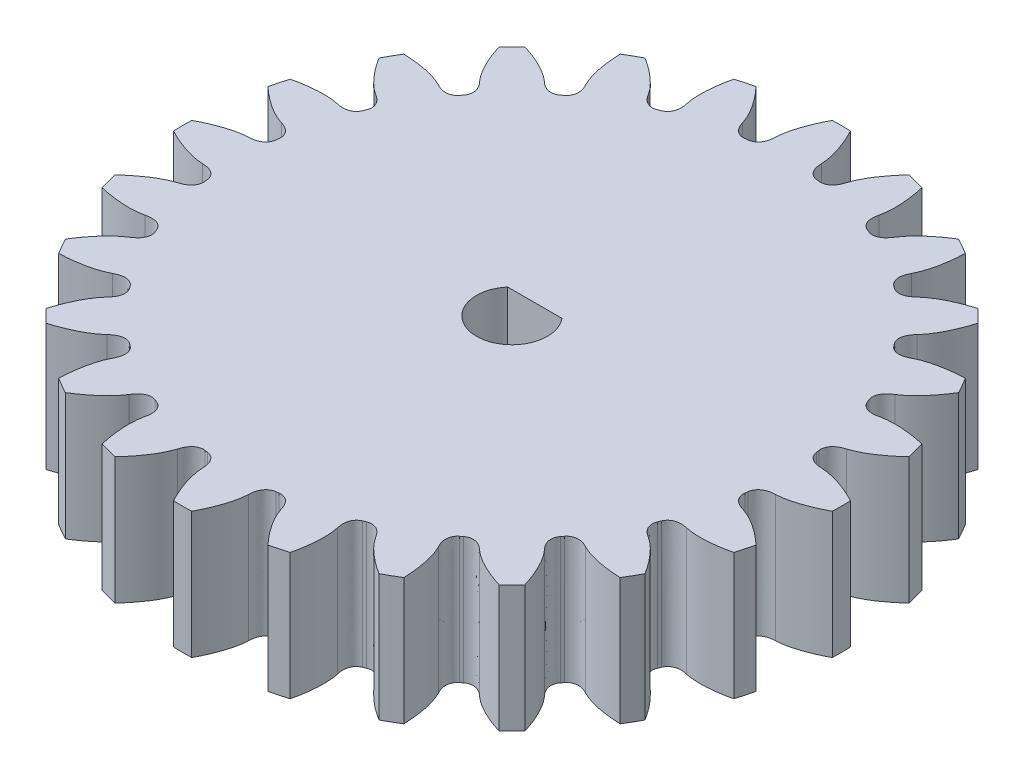
SolidWorks part; units mm, degrees
ref_plane "Спереди" through (0, 0, 0) normal (0, 0, 1) x (1, 0, 0)
ref_plane "Сверху" through (0, 0, 0) normal (0, 1, 0) x (1, 0, 0)
ref_plane "Справа" through (0, 0, 0) normal (1, 0, 0) x (0, 0, -1)
sketch "Эскиз1" plane through (0, 0, 0) normal (0, 1, 0) x (1, 0, 0)
  line L0 (-1.0724, 0.9) -> (1.0724, 0.9)
  arc A3 (-1.0724, 0.9) -> (1.0724, 0.9) centre (0, 0) ccw
  point P1 (0, -1.4)
  line B0 (-14.3, 0) -> (14.3, 0) construction
  line B1 (0, -14.3) -> (0, 14.3) construction
  arc B2 (0.3577, 12.9951) -> (-0.3577, 12.9951) centre (0, 0) ccw
  arc B3 (-1.346, 10.6654) -> (-1.4603, 10.6504) centre (0, 0) ccw
  arc B4 (-3.0178, 12.6449) -> (-3.7089, 12.4597) centre (0, 0) ccw
  arc B5 (-4.0605, 9.9536) -> (-4.1671, 9.9095) centre (0, 0) ccw
  arc B6 (-6.1877, 11.4329) -> (-6.8073, 11.0752) centre (0, 0) ccw
  arc B7 (-6.4984, 8.5635) -> (-6.5898, 8.4933) centre (0, 0) ccw
  arc B8 (-8.936, 9.4419) -> (-9.4419, 8.936) centre (0, 0) ccw
  arc B9 (-8.4933, 6.5898) -> (-8.5635, 6.4984) centre (0, 0) ccw
  arc B10 (-11.0752, 6.8073) -> (-11.4329, 6.1877) centre (0, 0) ccw
  arc B11 (-9.9095, 4.1671) -> (-9.9536, 4.0605) centre (0, 0) ccw
  arc B12 (-12.4597, 3.7089) -> (-12.6449, 3.0178) centre (0, 0) ccw
  arc B13 (-10.6504, 1.4603) -> (-10.6654, 1.346) centre (0, 0) ccw
  arc B14 (-12.9951, 0.3577) -> (-12.9951, -0.3577) centre (0, 0) ccw
  arc B15 (-10.6654, -1.346) -> (-10.6504, -1.4603) centre (0, 0) ccw
  arc B16 (-12.6449, -3.0178) -> (-12.4597, -3.7089) centre (0, 0) ccw
  arc B17 (-9.9536, -4.0605) -> (-9.9095, -4.1671) centre (0, 0) ccw
  arc B18 (-11.4329, -6.1877) -> (-11.0752, -6.8073) centre (0, 0) ccw
  arc B19 (-8.5635, -6.4984) -> (-8.4933, -6.5898) centre (0, 0) ccw
  arc B20 (-9.4419, -8.936) -> (-8.936, -9.4419) centre (0, 0) ccw
  arc B21 (-6.5898, -8.4933) -> (-6.4984, -8.5635) centre (0, 0) ccw
  arc B22 (-6.8073, -11.0752) -> (-6.1877, -11.4329) centre (0, 0) ccw
  arc B23 (-4.1671, -9.9095) -> (-4.0605, -9.9536) centre (0, 0) ccw
  arc B24 (-3.7089, -12.4597) -> (-3.0178, -12.6449) centre (0, 0) ccw
  arc B25 (-1.4603, -10.6504) -> (-1.346, -10.6654) centre (0, 0) ccw
  arc B26 (-0.3577, -12.9951) -> (0.3577, -12.9951) centre (0, 0) ccw
  arc B27 (1.346, -10.6654) -> (1.4603, -10.6504) centre (0, 0) ccw
  arc B28 (3.0178, -12.6449) -> (3.7089, -12.4597) centre (0, 0) ccw
  arc B29 (4.0605, -9.9536) -> (4.1671, -9.9095) centre (0, 0) ccw
  arc B30 (6.1877, -11.4329) -> (6.8073, -11.0752) centre (0, 0) ccw
  arc B31 (6.4984, -8.5635) -> (6.5898, -8.4933) centre (0, 0) ccw
  arc B32 (8.936, -9.4419) -> (9.4419, -8.936) centre (0, 0) ccw
  arc B33 (8.4933, -6.5898) -> (8.5635, -6.4984) centre (0, 0) ccw
  arc B34 (11.0752, -6.8073) -> (11.4329, -6.1877) centre (0, 0) ccw
  arc B35 (9.9095, -4.1671) -> (9.9536, -4.0605) centre (0, 0) ccw
  arc B36 (12.4597, -3.7089) -> (12.6449, -3.0178) centre (0, 0) ccw
  arc B37 (10.6504, -1.4603) -> (10.6654, -1.346) centre (0, 0) ccw
  arc B38 (12.9951, -0.3577) -> (12.9951, 0.3577) centre (0, 0) ccw
  arc B39 (10.6654, 1.346) -> (10.6504, 1.4603) centre (0, 0) ccw
  arc B40 (12.6449, 3.0178) -> (12.4597, 3.7089) centre (0, 0) ccw
  arc B41 (9.9536, 4.0605) -> (9.9095, 4.1671) centre (0, 0) ccw
  arc B42 (11.4329, 6.1877) -> (11.0752, 6.8073) centre (0, 0) ccw
  arc B43 (8.5635, 6.4984) -> (8.4933, 6.5898) centre (0, 0) ccw
  arc B44 (9.4419, 8.936) -> (8.936, 9.4419) centre (0, 0) ccw
  arc B45 (6.5898, 8.4933) -> (6.4984, 8.5635) centre (0, 0) ccw
  arc B46 (6.8073, 11.0752) -> (6.1877, 11.4329) centre (0, 0) ccw
  arc B47 (4.1671, 9.9095) -> (4.0605, 9.9536) centre (0, 0) ccw
  arc B48 (3.7089, 12.4597) -> (3.0178, 12.6449) centre (0, 0) ccw
  arc B49 (1.4603, 10.6504) -> (1.346, 10.6654) centre (0, 0) ccw
  circle B50 centre (0, 0) radius 12 construction
  spline B51 degree 3 poles (0.9058, 11.3017) (0.9058, 11.2304) (0.9138, 11.1608) (0.9299, 11.0929) (0.9396, 11.0522) (0.9513, 11.0113) (0.9676, 10.9727) (0.9799, 10.9437) (0.994, 10.915) (1.0107, 10.8883) (1.0248, 10.8656) (1.0406, 10.8436) (1.058, 10.8234) (1.0738, 10.805) (1.091, 10.7875) (1.1093, 10.7717) (1.1266, 10.7569) (1.1451, 10.7431) (1.1643, 10.7309) (1.1829, 10.7192) (1.2025, 10.7087) (1.2225, 10.6998) (1.2421, 10.6911) (1.2626, 10.6838) (1.2833, 10.678) (1.3038, 10.6723) (1.3247, 10.6681) (1.346, 10.6654) knots 0 0 0 0 1 1 1 2 2 2 3 3 3 4 4 4 5 5 5 6 6 6 7 7 7 8 8 8 9 9 9 9
  spline B52 degree 3 poles (-0.9058, 11.3017) (-0.9058, 11.2304) (-0.9138, 11.1608) (-0.9299, 11.0929) (-0.9396, 11.0522) (-0.9513, 11.0113) (-0.9676, 10.9727) (-0.9799, 10.9437) (-0.994, 10.915) (-1.0107, 10.8883) (-1.0248, 10.8656) (-1.0406, 10.8436) (-1.058, 10.8234) (-1.0738, 10.805) (-1.091, 10.7875) (-1.1093, 10.7717) (-1.1266, 10.7569) (-1.1451, 10.7431) (-1.1643, 10.7309) (-1.1829, 10.7192) (-1.2025, 10.7087) (-1.2225, 10.6998) (-1.2421, 10.6911) (-1.2626, 10.6838) (-1.2833, 10.678) (-1.3038, 10.6723) (-1.3247, 10.6681) (-1.346, 10.6654) knots 0 0 0 0 1 1 1 2 2 2 3 3 3 4 4 4 5 5 5 6 6 6 7 7 7 8 8 8 9 9 9 9
  spline B53 degree 3 poles (0.9058, 11.3017) (0.9032, 11.3642) (0.898, 11.4263) (0.8903, 11.4882) (0.8824, 11.551) (0.8712, 11.6136) (0.8589, 11.6757) (0.8463, 11.7389) (0.8314, 11.8016) (0.8153, 11.864) (0.7989, 11.9273) (0.7806, 11.9902) (0.7612, 12.0526) (0.7414, 12.116) (0.72, 12.179) (0.6975, 12.2415) (0.6746, 12.3049) (0.6503, 12.3678) (0.6249, 12.4303) (0.5991, 12.4937) (0.572, 12.5566) (0.5439, 12.6189) (0.5153, 12.6822) (0.4855, 12.745) (0.4547, 12.8073) (0.4235, 12.8704) (0.3912, 12.933) (0.3577, 12.9951) knots 0 0 0 0 1 1 1 2 2 2 3 3 3 4 4 4 5 5 5 6 6 6 7 7 7 8 8 8 9 9 9 9
  spline B54 degree 3 poles (-0.9058, 11.3017) (-0.9032, 11.3642) (-0.898, 11.4263) (-0.8903, 11.4882) (-0.8824, 11.551) (-0.8712, 11.6136) (-0.8589, 11.6757) (-0.8463, 11.7389) (-0.8314, 11.8016) (-0.8153, 11.864) (-0.7989, 11.9273) (-0.7806, 11.9902) (-0.7612, 12.0526) (-0.7414, 12.116) (-0.72, 12.179) (-0.6975, 12.2415) (-0.6746, 12.3049) (-0.6503, 12.3678) (-0.6249, 12.4303) (-0.5991, 12.4937) (-0.572, 12.5566) (-0.5439, 12.6189) (-0.5153, 12.6822) (-0.4855, 12.745) (-0.4547, 12.8073) (-0.4235, 12.8704) (-0.3912, 12.933) (-0.3577, 12.9951) knots 0 0 0 0 1 1 1 2 2 2 3 3 3 4 4 4 5 5 5 6 6 6 7 7 7 8 8 8 9 9 9 9
  spline B55 degree 3 poles (-2.0502, 11.151) (-2.0317, 11.0822) (-2.0059, 11.017) (-1.9728, 10.9556) (-1.9529, 10.9188) (-1.931, 10.8823) (-1.9053, 10.8493) (-1.886, 10.8244) (-1.8649, 10.8004) (-1.8419, 10.7789) (-1.8224, 10.7606) (-1.8014, 10.7435) (-1.7793, 10.7284) (-1.7594, 10.7148) (-1.7382, 10.7023) (-1.7164, 10.6918) (-1.6959, 10.6819) (-1.6745, 10.6734) (-1.6527, 10.6666) (-1.6318, 10.6601) (-1.6101, 10.655) (-1.5885, 10.6516) (-1.5672, 10.6483) (-1.5456, 10.6465) (-1.5241, 10.6463) (-1.5028, 10.6461) (-1.4816, 10.6475) (-1.4603, 10.6504) knots 0 0 0 0 1 1 1 2 2 2 3 3 3 4 4 4 5 5 5 6 6 6 7 7 7 8 8 8 9 9 9 9
  spline B56 degree 3 poles (-3.8, 10.6822) (-3.7815, 10.6133) (-3.7713, 10.544) (-3.7693, 10.4743) (-3.7681, 10.4325) (-3.7688, 10.3898) (-3.7746, 10.3484) (-3.7789, 10.3172) (-3.7852, 10.2858) (-3.7943, 10.2557) (-3.8021, 10.2302) (-3.8117, 10.2048) (-3.8232, 10.1807) (-3.8337, 10.1589) (-3.8458, 10.1376) (-3.8595, 10.1176) (-3.8723, 10.0988) (-3.8866, 10.0806) (-3.902, 10.0639) (-3.9169, 10.0478) (-3.9331, 10.0326) (-3.9502, 10.0188) (-3.9669, 10.0053) (-3.9848, 9.9929) (-4.0032, 9.982) (-4.0216, 9.9712) (-4.0406, 9.9618) (-4.0605, 9.9536) knots 0 0 0 0 1 1 1 2 2 2 3 3 3 4 4 4 5 5 5 6 6 6 7 7 7 8 8 8 9 9 9 9
  spline B57 degree 3 poles (-2.0502, 11.151) (-2.0689, 11.2107) (-2.09, 11.2694) (-2.1134, 11.3271) (-2.1373, 11.3858) (-2.1643, 11.4434) (-2.1923, 11.5002) (-2.2208, 11.5579) (-2.2514, 11.6147) (-2.2831, 11.6707) (-2.3153, 11.7276) (-2.3493, 11.7837) (-2.3842, 11.8389) (-2.4197, 11.8951) (-2.4567, 11.9503) (-2.4946, 12.0049) (-2.5331, 12.0602) (-2.5729, 12.1147) (-2.6136, 12.1685) (-2.6549, 12.223) (-2.6974, 12.2768) (-2.7407, 12.3297) (-2.7847, 12.3835) (-2.8297, 12.4364) (-2.8755, 12.4885) (-2.9221, 12.5415) (-2.9695, 12.5936) (-3.0178, 12.6449) knots 0 0 0 0 1 1 1 2 2 2 3 3 3 4 4 4 5 5 5 6 6 6 7 7 7 8 8 8 9 9 9 9
  spline B58 degree 3 poles (-3.8, 10.6822) (-3.8136, 10.7432) (-3.8247, 10.8046) (-3.8333, 10.8663) (-3.842, 10.929) (-3.8474, 10.9924) (-3.8515, 11.0556) (-3.8557, 11.1198) (-3.8576, 11.1843) (-3.8581, 11.2487) (-3.8587, 11.3141) (-3.8573, 11.3796) (-3.8547, 11.4449) (-3.852, 11.5113) (-3.8476, 11.5776) (-3.8421, 11.6438) (-3.8364, 11.711) (-3.8292, 11.7781) (-3.8208, 11.845) (-3.8123, 11.9129) (-3.8024, 11.9807) (-3.7914, 12.0482) (-3.7802, 12.1167) (-3.7676, 12.1851) (-3.754, 12.2532) (-3.7402, 12.3223) (-3.7251, 12.3911) (-3.7089, 12.4597) knots 0 0 0 0 1 1 1 2 2 2 3 3 3 4 4 4 5 5 5 6 6 6 7 7 7 8 8 8 9 9 9 9
  spline B59 degree 3 poles (-4.8664, 10.2404) (-4.8308, 10.1787) (-4.789, 10.1225) (-4.7411, 10.0717) (-4.7124, 10.0413) (-4.6817, 10.0117) (-4.6484, 9.9865) (-4.6233, 9.9675) (-4.5967, 9.9497) (-4.5689, 9.9349) (-4.5453, 9.9223) (-4.5206, 9.9111) (-4.4954, 9.9023) (-4.4726, 9.8943) (-4.4489, 9.8878) (-4.4252, 9.8833) (-4.4028, 9.879) (-4.3799, 9.8763) (-4.3571, 9.8754) (-4.3352, 9.8745) (-4.313, 9.8752) (-4.2912, 9.8776) (-4.2698, 9.8798) (-4.2484, 9.8837) (-4.2276, 9.8891) (-4.2071, 9.8944) (-4.1869, 9.9012) (-4.1671, 9.9095) knots 0 0 0 0 1 1 1 2 2 2 3 3 3 4 4 4 5 5 5 6 6 6 7 7 7 8 8 8 9 9 9 9
  spline B60 degree 3 poles (-6.4353, 9.3347) (-6.3996, 9.2729) (-6.3718, 9.2086) (-6.3518, 9.1418) (-6.3398, 9.1017) (-6.3295, 9.0604) (-6.3243, 9.0188) (-6.3204, 8.9876) (-6.3184, 8.9557) (-6.3194, 8.9242) (-6.3203, 8.8975) (-6.323, 8.8706) (-6.3279, 8.8443) (-6.3324, 8.8205) (-6.3386, 8.7968) (-6.3466, 8.7739) (-6.3541, 8.7524) (-6.3632, 8.7312) (-6.3738, 8.7111) (-6.384, 8.6917) (-6.3957, 8.6728) (-6.4086, 8.655) (-6.4213, 8.6377) (-6.4353, 8.6211) (-6.4504, 8.6058) (-6.4653, 8.5906) (-6.4813, 8.5765) (-6.4984, 8.5635) knots 0 0 0 0 1 1 1 2 2 2 3 3 3 4 4 4 5 5 5 6 6 6 7 7 7 8 8 8 9 9 9 9
  spline B61 degree 3 poles (-4.8664, 10.2404) (-4.8999, 10.2932) (-4.9355, 10.3445) (-4.9731, 10.3942) (-5.0113, 10.4447) (-5.0523, 10.4933) (-5.0941, 10.5409) (-5.1365, 10.5893) (-5.1808, 10.6362) (-5.2259, 10.6822) (-5.2718, 10.7288) (-5.319, 10.7741) (-5.3671, 10.8185) (-5.4159, 10.8635) (-5.4659, 10.9073) (-5.5167, 10.9502) (-5.5682, 10.9937) (-5.6207, 11.036) (-5.674, 11.0774) (-5.728, 11.1194) (-5.7829, 11.1603) (-5.8385, 11.2003) (-5.8949, 11.2408) (-5.9521, 11.2803) (-6.0098, 11.3188) (-6.0685, 11.3578) (-6.1278, 11.3959) (-6.1877, 11.4329) knots 0 0 0 0 1 1 1 2 2 2 3 3 3 4 4 4 5 5 5 6 6 6 7 7 7 8 8 8 9 9 9 9
  spline B62 degree 3 poles (-6.4353, 9.3347) (-6.4642, 9.3901) (-6.4908, 9.4465) (-6.5151, 9.5039) (-6.5397, 9.5623) (-6.5613, 9.622) (-6.5817, 9.6821) (-6.6024, 9.743) (-6.6209, 9.8048) (-6.638, 9.8669) (-6.6555, 9.9299) (-6.6711, 9.9935) (-6.6855, 10.0573) (-6.7001, 10.1221) (-6.713, 10.1873) (-6.7248, 10.2527) (-6.7367, 10.319) (-6.7471, 10.3857) (-6.7563, 10.4525) (-6.7657, 10.5203) (-6.7737, 10.5883) (-6.7805, 10.6564) (-6.7874, 10.7255) (-6.793, 10.7948) (-6.7974, 10.8641) (-6.8019, 10.9344) (-6.8053, 11.0047) (-6.8073, 11.0752) knots 0 0 0 0 1 1 1 2 2 2 3 3 3 4 4 4 5 5 5 6 6 6 7 7 7 8 8 8 9 9 9 9
  spline B63 degree 3 poles (-7.351, 8.632) (-7.3006, 8.5816) (-7.2457, 8.5381) (-7.1863, 8.5015) (-7.1507, 8.4795) (-7.1134, 8.4588) (-7.0747, 8.4431) (-7.0455, 8.4312) (-7.0152, 8.421) (-6.9845, 8.4138) (-6.9585, 8.4078) (-6.9318, 8.4034) (-6.9052, 8.4014) (-6.881, 8.3996) (-6.8565, 8.3994) (-6.8324, 8.4012) (-6.8097, 8.4029) (-6.7868, 8.4062) (-6.7646, 8.4112) (-6.7432, 8.416) (-6.7219, 8.4224) (-6.7015, 8.4304) (-6.6814, 8.4381) (-6.6618, 8.4474) (-6.6431, 8.4579) (-6.6246, 8.4684) (-6.6068, 8.4802) (-6.5898, 8.4933) knots 0 0 0 0 1 1 1 2 2 2 3 3 3 4 4 4 5 5 5 6 6 6 7 7 7 8 8 8 9 9 9 9
  spline B64 degree 3 poles (-8.632, 7.351) (-8.5816, 7.3006) (-8.5381, 7.2457) (-8.5015, 7.1863) (-8.4795, 7.1507) (-8.4588, 7.1134) (-8.4431, 7.0747) (-8.4312, 7.0455) (-8.421, 7.0152) (-8.4138, 6.9845) (-8.4078, 6.9585) (-8.4034, 6.9318) (-8.4014, 6.9052) (-8.3996, 6.881) (-8.3994, 6.8565) (-8.4012, 6.8324) (-8.4029, 6.8097) (-8.4062, 6.7868) (-8.4112, 6.7646) (-8.416, 6.7432) (-8.4224, 6.7219) (-8.4304, 6.7015) (-8.4381, 6.6814) (-8.4474, 6.6618) (-8.4579, 6.6431) (-8.4684, 6.6246) (-8.4802, 6.6068) (-8.4933, 6.5898) knots 0 0 0 0 1 1 1 2 2 2 3 3 3 4 4 4 5 5 5 6 6 6 7 7 7 8 8 8 9 9 9 9
  spline B65 degree 3 poles (-7.351, 8.632) (-7.3971, 8.6743) (-7.4447, 8.7146) (-7.4938, 8.7529) (-7.5438, 8.7918) (-7.596, 8.8281) (-7.6487, 8.8633) (-7.7022, 8.8991) (-7.7571, 8.9329) (-7.8126, 8.9656) (-7.869, 8.9988) (-7.9263, 9.0303) (-7.9843, 9.0607) (-8.0431, 9.0916) (-8.1027, 9.121) (-8.1628, 9.1492) (-8.2238, 9.1779) (-8.2855, 9.2052) (-8.3477, 9.2314) (-8.4107, 9.258) (-8.4744, 9.2833) (-8.5384, 9.3075) (-8.6033, 9.3321) (-8.6688, 9.3554) (-8.7346, 9.3776) (-8.8013, 9.4002) (-8.8684, 9.4216) (-8.936, 9.4419) knots 0 0 0 0 1 1 1 2 2 2 3 3 3 4 4 4 5 5 5 6 6 6 7 7 7 8 8 8 9 9 9 9
  spline B66 degree 3 poles (-8.632, 7.351) (-8.6743, 7.3971) (-8.7146, 7.4447) (-8.7529, 7.4938) (-8.7918, 7.5438) (-8.8281, 7.596) (-8.8633, 7.6487) (-8.8991, 7.7022) (-8.9329, 7.7571) (-8.9656, 7.8126) (-8.9988, 7.869) (-9.0303, 7.9263) (-9.0607, 7.9843) (-9.0916, 8.0431) (-9.121, 8.1027) (-9.1492, 8.1628) (-9.1779, 8.2238) (-9.2052, 8.2855) (-9.2314, 8.3477) (-9.258, 8.4107) (-9.2833, 8.4744) (-9.3075, 8.5384) (-9.3321, 8.6033) (-9.3554, 8.6688) (-9.3776, 8.7346) (-9.4002, 8.8013) (-9.4216, 8.8684) (-9.4419, 8.936) knots 0 0 0 0 1 1 1 2 2 2 3 3 3 4 4 4 5 5 5 6 6 6 7 7 7 8 8 8 9 9 9 9
  spline B67 degree 3 poles (-9.3347, 6.4353) (-9.2729, 6.3996) (-9.2086, 6.3718) (-9.1418, 6.3518) (-9.1017, 6.3398) (-9.0604, 6.3295) (-9.0188, 6.3243) (-8.9876, 6.3204) (-8.9557, 6.3184) (-8.9242, 6.3194) (-8.8975, 6.3203) (-8.8706, 6.323) (-8.8443, 6.3279) (-8.8205, 6.3324) (-8.7968, 6.3386) (-8.7739, 6.3466) (-8.7524, 6.3541) (-8.7312, 6.3632) (-8.7111, 6.3738) (-8.6917, 6.384) (-8.6728, 6.3957) (-8.655, 6.4086) (-8.6377, 6.4213) (-8.6211, 6.4353) (-8.6058, 6.4504) (-8.5906, 6.4653) (-8.5765, 6.4813) (-8.5635, 6.4984) knots 0 0 0 0 1 1 1 2 2 2 3 3 3 4 4 4 5 5 5 6 6 6 7 7 7 8 8 8 9 9 9 9
  spline B68 degree 3 poles (-10.2404, 4.8664) (-10.1787, 4.8308) (-10.1225, 4.789) (-10.0717, 4.7411) (-10.0413, 4.7124) (-10.0117, 4.6817) (-9.9865, 4.6484) (-9.9675, 4.6233) (-9.9497, 4.5967) (-9.9349, 4.5689) (-9.9223, 4.5453) (-9.9111, 4.5206) (-9.9023, 4.4954) (-9.8943, 4.4726) (-9.8878, 4.4489) (-9.8833, 4.4252) (-9.879, 4.4028) (-9.8763, 4.3799) (-9.8754, 4.3571) (-9.8745, 4.3352) (-9.8752, 4.313) (-9.8776, 4.2912) (-9.8798, 4.2698) (-9.8837, 4.2484) (-9.8891, 4.2276) (-9.8944, 4.2071) (-9.9012, 4.1869) (-9.9095, 4.1671) knots 0 0 0 0 1 1 1 2 2 2 3 3 3 4 4 4 5 5 5 6 6 6 7 7 7 8 8 8 9 9 9 9
  spline B69 degree 3 poles (-9.3347, 6.4353) (-9.3901, 6.4642) (-9.4465, 6.4908) (-9.5039, 6.5151) (-9.5623, 6.5397) (-9.622, 6.5613) (-9.6821, 6.5817) (-9.743, 6.6024) (-9.8048, 6.6209) (-9.8669, 6.638) (-9.9299, 6.6555) (-9.9935, 6.6711) (-10.0573, 6.6855) (-10.1221, 6.7001) (-10.1873, 6.713) (-10.2527, 6.7248) (-10.319, 6.7367) (-10.3857, 6.7471) (-10.4525, 6.7563) (-10.5203, 6.7657) (-10.5883, 6.7737) (-10.6564, 6.7805) (-10.7255, 6.7874) (-10.7948, 6.793) (-10.8641, 6.7974) (-10.9344, 6.8019) (-11.0047, 6.8053) (-11.0752, 6.8073) knots 0 0 0 0 1 1 1 2 2 2 3 3 3 4 4 4 5 5 5 6 6 6 7 7 7 8 8 8 9 9 9 9
  spline B70 degree 3 poles (-10.2404, 4.8664) (-10.2932, 4.8999) (-10.3445, 4.9355) (-10.3942, 4.9731) (-10.4447, 5.0113) (-10.4933, 5.0523) (-10.5409, 5.0941) (-10.5893, 5.1365) (-10.6362, 5.1808) (-10.6822, 5.2259) (-10.7288, 5.2718) (-10.7741, 5.319) (-10.8185, 5.3671) (-10.8635, 5.4159) (-10.9073, 5.4659) (-10.9502, 5.5167) (-10.9937, 5.5682) (-11.036, 5.6207) (-11.0774, 5.674) (-11.1194, 5.728) (-11.1603, 5.7829) (-11.2003, 5.8385) (-11.2408, 5.8949) (-11.2803, 5.9521) (-11.3188, 6.0098) (-11.3578, 6.0685) (-11.3959, 6.1278) (-11.4329, 6.1877) knots 0 0 0 0 1 1 1 2 2 2 3 3 3 4 4 4 5 5 5 6 6 6 7 7 7 8 8 8 9 9 9 9
  spline B71 degree 3 poles (-10.6822, 3.8) (-10.6133, 3.7815) (-10.544, 3.7713) (-10.4743, 3.7693) (-10.4325, 3.7681) (-10.3898, 3.7688) (-10.3484, 3.7746) (-10.3172, 3.7789) (-10.2858, 3.7852) (-10.2557, 3.7943) (-10.2302, 3.8021) (-10.2048, 3.8117) (-10.1807, 3.8232) (-10.1589, 3.8337) (-10.1376, 3.8458) (-10.1176, 3.8595) (-10.0988, 3.8723) (-10.0806, 3.8866) (-10.0639, 3.902) (-10.0478, 3.9169) (-10.0326, 3.9331) (-10.0188, 3.9502) (-10.0053, 3.9669) (-9.9929, 3.9848) (-9.982, 4.0032) (-9.9712, 4.0216) (-9.9618, 4.0406) (-9.9536, 4.0605) knots 0 0 0 0 1 1 1 2 2 2 3 3 3 4 4 4 5 5 5 6 6 6 7 7 7 8 8 8 9 9 9 9
  spline B72 degree 3 poles (-11.151, 2.0502) (-11.0822, 2.0317) (-11.017, 2.0059) (-10.9556, 1.9728) (-10.9188, 1.9529) (-10.8823, 1.931) (-10.8493, 1.9053) (-10.8244, 1.886) (-10.8004, 1.8649) (-10.7789, 1.8419) (-10.7606, 1.8224) (-10.7435, 1.8014) (-10.7284, 1.7793) (-10.7148, 1.7594) (-10.7023, 1.7382) (-10.6918, 1.7164) (-10.6819, 1.6959) (-10.6734, 1.6745) (-10.6666, 1.6527) (-10.6601, 1.6318) (-10.655, 1.6101) (-10.6516, 1.5885) (-10.6483, 1.5672) (-10.6465, 1.5456) (-10.6463, 1.5241) (-10.6461, 1.5028) (-10.6475, 1.4816) (-10.6504, 1.4603) knots 0 0 0 0 1 1 1 2 2 2 3 3 3 4 4 4 5 5 5 6 6 6 7 7 7 8 8 8 9 9 9 9
  spline B73 degree 3 poles (-10.6822, 3.8) (-10.7432, 3.8136) (-10.8046, 3.8247) (-10.8663, 3.8333) (-10.929, 3.842) (-10.9924, 3.8474) (-11.0556, 3.8515) (-11.1198, 3.8557) (-11.1843, 3.8576) (-11.2487, 3.8581) (-11.3141, 3.8587) (-11.3796, 3.8573) (-11.4449, 3.8547) (-11.5113, 3.852) (-11.5776, 3.8476) (-11.6438, 3.8421) (-11.711, 3.8364) (-11.7781, 3.8292) (-11.845, 3.8208) (-11.9129, 3.8123) (-11.9807, 3.8024) (-12.0482, 3.7914) (-12.1167, 3.7802) (-12.1851, 3.7676) (-12.2532, 3.754) (-12.3223, 3.7402) (-12.3911, 3.7251) (-12.4597, 3.7089) knots 0 0 0 0 1 1 1 2 2 2 3 3 3 4 4 4 5 5 5 6 6 6 7 7 7 8 8 8 9 9 9 9
  spline B74 degree 3 poles (-11.151, 2.0502) (-11.2107, 2.0689) (-11.2694, 2.09) (-11.3271, 2.1134) (-11.3858, 2.1373) (-11.4434, 2.1643) (-11.5002, 2.1923) (-11.5579, 2.2208) (-11.6147, 2.2514) (-11.6707, 2.2831) (-11.7276, 2.3153) (-11.7837, 2.3493) (-11.8389, 2.3842) (-11.8951, 2.4197) (-11.9503, 2.4567) (-12.0049, 2.4946) (-12.0602, 2.5331) (-12.1147, 2.5729) (-12.1685, 2.6136) (-12.223, 2.6549) (-12.2768, 2.6974) (-12.3297, 2.7407) (-12.3835, 2.7847) (-12.4364, 2.8297) (-12.4885, 2.8755) (-12.5415, 2.9221) (-12.5936, 2.9695) (-12.6449, 3.0178) knots 0 0 0 0 1 1 1 2 2 2 3 3 3 4 4 4 5 5 5 6 6 6 7 7 7 8 8 8 9 9 9 9
  spline B75 degree 3 poles (-11.3017, 0.9058) (-11.2304, 0.9058) (-11.1608, 0.9138) (-11.0929, 0.9299) (-11.0522, 0.9396) (-11.0113, 0.9513) (-10.9727, 0.9676) (-10.9437, 0.9799) (-10.915, 0.994) (-10.8883, 1.0107) (-10.8656, 1.0248) (-10.8436, 1.0406) (-10.8234, 1.058) (-10.805, 1.0738) (-10.7875, 1.091) (-10.7717, 1.1093) (-10.7569, 1.1266) (-10.7431, 1.1451) (-10.7309, 1.1643) (-10.7192, 1.1829) (-10.7087, 1.2025) (-10.6998, 1.2225) (-10.6911, 1.2421) (-10.6838, 1.2626) (-10.678, 1.2833) (-10.6723, 1.3038) (-10.6681, 1.3247) (-10.6654, 1.346) knots 0 0 0 0 1 1 1 2 2 2 3 3 3 4 4 4 5 5 5 6 6 6 7 7 7 8 8 8 9 9 9 9
  spline B76 degree 3 poles (-11.3017, -0.9058) (-11.2304, -0.9058) (-11.1608, -0.9138) (-11.0929, -0.9299) (-11.0522, -0.9396) (-11.0113, -0.9513) (-10.9727, -0.9676) (-10.9437, -0.9799) (-10.915, -0.994) (-10.8883, -1.0107) (-10.8656, -1.0248) (-10.8436, -1.0406) (-10.8234, -1.058) (-10.805, -1.0738) (-10.7875, -1.091) (-10.7717, -1.1093) (-10.7569, -1.1266) (-10.7431, -1.1451) (-10.7309, -1.1643) (-10.7192, -1.1829) (-10.7087, -1.2025) (-10.6998, -1.2225) (-10.6911, -1.2421) (-10.6838, -1.2626) (-10.678, -1.2833) (-10.6723, -1.3038) (-10.6681, -1.3247) (-10.6654, -1.346) knots 0 0 0 0 1 1 1 2 2 2 3 3 3 4 4 4 5 5 5 6 6 6 7 7 7 8 8 8 9 9 9 9
  spline B77 degree 3 poles (-11.3017, 0.9058) (-11.3642, 0.9032) (-11.4263, 0.898) (-11.4882, 0.8903) (-11.551, 0.8824) (-11.6136, 0.8712) (-11.6757, 0.8589) (-11.7389, 0.8463) (-11.8016, 0.8314) (-11.864, 0.8153) (-11.9273, 0.7989) (-11.9902, 0.7806) (-12.0526, 0.7612) (-12.116, 0.7414) (-12.179, 0.72) (-12.2415, 0.6975) (-12.3049, 0.6746) (-12.3678, 0.6503) (-12.4303, 0.6249) (-12.4937, 0.5991) (-12.5566, 0.572) (-12.6189, 0.5439) (-12.6822, 0.5153) (-12.745, 0.4855) (-12.8073, 0.4547) (-12.8704, 0.4235) (-12.933, 0.3912) (-12.9951, 0.3577) knots 0 0 0 0 1 1 1 2 2 2 3 3 3 4 4 4 5 5 5 6 6 6 7 7 7 8 8 8 9 9 9 9
  spline B78 degree 3 poles (-11.3017, -0.9058) (-11.3642, -0.9032) (-11.4263, -0.898) (-11.4882, -0.8903) (-11.551, -0.8824) (-11.6136, -0.8712) (-11.6757, -0.8589) (-11.7389, -0.8463) (-11.8016, -0.8314) (-11.864, -0.8153) (-11.9273, -0.7989) (-11.9902, -0.7806) (-12.0526, -0.7612) (-12.116, -0.7414) (-12.179, -0.72) (-12.2415, -0.6975) (-12.3049, -0.6746) (-12.3678, -0.6503) (-12.4303, -0.6249) (-12.4937, -0.5991) (-12.5566, -0.572) (-12.6189, -0.5439) (-12.6822, -0.5153) (-12.745, -0.4855) (-12.8073, -0.4547) (-12.8704, -0.4235) (-12.933, -0.3912) (-12.9951, -0.3577) knots 0 0 0 0 1 1 1 2 2 2 3 3 3 4 4 4 5 5 5 6 6 6 7 7 7 8 8 8 9 9 9 9
  spline B79 degree 3 poles (-11.151, -2.0502) (-11.0822, -2.0317) (-11.017, -2.0059) (-10.9556, -1.9728) (-10.9188, -1.9529) (-10.8823, -1.931) (-10.8493, -1.9053) (-10.8244, -1.886) (-10.8004, -1.8649) (-10.7789, -1.8419) (-10.7606, -1.8224) (-10.7435, -1.8014) (-10.7284, -1.7793) (-10.7148, -1.7594) (-10.7023, -1.7382) (-10.6918, -1.7164) (-10.6819, -1.6959) (-10.6734, -1.6745) (-10.6666, -1.6527) (-10.6601, -1.6318) (-10.655, -1.6101) (-10.6516, -1.5885) (-10.6483, -1.5672) (-10.6465, -1.5456) (-10.6463, -1.5241) (-10.6461, -1.5028) (-10.6475, -1.4816) (-10.6504, -1.4603) knots 0 0 0 0 1 1 1 2 2 2 3 3 3 4 4 4 5 5 5 6 6 6 7 7 7 8 8 8 9 9 9 9
  spline B80 degree 3 poles (-10.6822, -3.8) (-10.6133, -3.7815) (-10.544, -3.7713) (-10.4743, -3.7693) (-10.4325, -3.7681) (-10.3898, -3.7688) (-10.3484, -3.7746) (-10.3172, -3.7789) (-10.2858, -3.7852) (-10.2557, -3.7943) (-10.2302, -3.8021) (-10.2048, -3.8117) (-10.1807, -3.8232) (-10.1589, -3.8337) (-10.1376, -3.8458) (-10.1176, -3.8595) (-10.0988, -3.8723) (-10.0806, -3.8866) (-10.0639, -3.902) (-10.0478, -3.9169) (-10.0326, -3.9331) (-10.0188, -3.9502) (-10.0053, -3.9669) (-9.9929, -3.9848) (-9.982, -4.0032) (-9.9712, -4.0216) (-9.9618, -4.0406) (-9.9536, -4.0605) knots 0 0 0 0 1 1 1 2 2 2 3 3 3 4 4 4 5 5 5 6 6 6 7 7 7 8 8 8 9 9 9 9
  spline B81 degree 3 poles (-11.151, -2.0502) (-11.2107, -2.0689) (-11.2694, -2.09) (-11.3271, -2.1134) (-11.3858, -2.1373) (-11.4434, -2.1643) (-11.5002, -2.1923) (-11.5579, -2.2208) (-11.6147, -2.2514) (-11.6707, -2.2831) (-11.7276, -2.3153) (-11.7837, -2.3493) (-11.8389, -2.3842) (-11.8951, -2.4197) (-11.9503, -2.4567) (-12.0049, -2.4946) (-12.0602, -2.5331) (-12.1147, -2.5729) (-12.1685, -2.6136) (-12.223, -2.6549) (-12.2768, -2.6974) (-12.3297, -2.7407) (-12.3835, -2.7847) (-12.4364, -2.8297) (-12.4885, -2.8755) (-12.5415, -2.9221) (-12.5936, -2.9695) (-12.6449, -3.0178) knots 0 0 0 0 1 1 1 2 2 2 3 3 3 4 4 4 5 5 5 6 6 6 7 7 7 8 8 8 9 9 9 9
  spline B82 degree 3 poles (-10.6822, -3.8) (-10.7432, -3.8136) (-10.8046, -3.8247) (-10.8663, -3.8333) (-10.929, -3.842) (-10.9924, -3.8474) (-11.0556, -3.8515) (-11.1198, -3.8557) (-11.1843, -3.8576) (-11.2487, -3.8581) (-11.3141, -3.8587) (-11.3796, -3.8573) (-11.4449, -3.8547) (-11.5113, -3.852) (-11.5776, -3.8476) (-11.6438, -3.8421) (-11.711, -3.8364) (-11.7781, -3.8292) (-11.845, -3.8208) (-11.9129, -3.8123) (-11.9807, -3.8024) (-12.0482, -3.7914) (-12.1167, -3.7802) (-12.1851, -3.7676) (-12.2532, -3.754) (-12.3223, -3.7402) (-12.3911, -3.7251) (-12.4597, -3.7089) knots 0 0 0 0 1 1 1 2 2 2 3 3 3 4 4 4 5 5 5 6 6 6 7 7 7 8 8 8 9 9 9 9
  spline B83 degree 3 poles (-10.2404, -4.8664) (-10.1787, -4.8308) (-10.1225, -4.789) (-10.0717, -4.7411) (-10.0413, -4.7124) (-10.0117, -4.6817) (-9.9865, -4.6484) (-9.9675, -4.6233) (-9.9497, -4.5967) (-9.9349, -4.5689) (-9.9223, -4.5453) (-9.9111, -4.5206) (-9.9023, -4.4954) (-9.8943, -4.4726) (-9.8878, -4.4489) (-9.8833, -4.4252) (-9.879, -4.4028) (-9.8763, -4.3799) (-9.8754, -4.3571) (-9.8745, -4.3352) (-9.8752, -4.313) (-9.8776, -4.2912) (-9.8798, -4.2698) (-9.8837, -4.2484) (-9.8891, -4.2276) (-9.8944, -4.2071) (-9.9012, -4.1869) (-9.9095, -4.1671) knots 0 0 0 0 1 1 1 2 2 2 3 3 3 4 4 4 5 5 5 6 6 6 7 7 7 8 8 8 9 9 9 9
  spline B84 degree 3 poles (-9.3347, -6.4353) (-9.2729, -6.3996) (-9.2086, -6.3718) (-9.1418, -6.3518) (-9.1017, -6.3398) (-9.0604, -6.3295) (-9.0188, -6.3243) (-8.9876, -6.3204) (-8.9557, -6.3184) (-8.9242, -6.3194) (-8.8975, -6.3203) (-8.8706, -6.323) (-8.8443, -6.3279) (-8.8205, -6.3324) (-8.7968, -6.3386) (-8.7739, -6.3466) (-8.7524, -6.3541) (-8.7312, -6.3632) (-8.7111, -6.3738) (-8.6917, -6.384) (-8.6728, -6.3957) (-8.655, -6.4086) (-8.6377, -6.4213) (-8.6211, -6.4353) (-8.6058, -6.4504) (-8.5906, -6.4653) (-8.5765, -6.4813) (-8.5635, -6.4984) knots 0 0 0 0 1 1 1 2 2 2 3 3 3 4 4 4 5 5 5 6 6 6 7 7 7 8 8 8 9 9 9 9
  spline B85 degree 3 poles (-10.2404, -4.8664) (-10.2932, -4.8999) (-10.3445, -4.9355) (-10.3942, -4.9731) (-10.4447, -5.0113) (-10.4933, -5.0523) (-10.5409, -5.0941) (-10.5893, -5.1365) (-10.6362, -5.1808) (-10.6822, -5.2259) (-10.7288, -5.2718) (-10.7741, -5.319) (-10.8185, -5.3671) (-10.8635, -5.4159) (-10.9073, -5.4659) (-10.9502, -5.5167) (-10.9937, -5.5682) (-11.036, -5.6207) (-11.0774, -5.674) (-11.1194, -5.728) (-11.1603, -5.7829) (-11.2003, -5.8385) (-11.2408, -5.8949) (-11.2803, -5.9521) (-11.3188, -6.0098) (-11.3578, -6.0685) (-11.3959, -6.1278) (-11.4329, -6.1877) knots 0 0 0 0 1 1 1 2 2 2 3 3 3 4 4 4 5 5 5 6 6 6 7 7 7 8 8 8 9 9 9 9
  spline B86 degree 3 poles (-9.3347, -6.4353) (-9.3901, -6.4642) (-9.4465, -6.4908) (-9.5039, -6.5151) (-9.5623, -6.5397) (-9.622, -6.5613) (-9.6821, -6.5817) (-9.743, -6.6024) (-9.8048, -6.6209) (-9.8669, -6.638) (-9.9299, -6.6555) (-9.9935, -6.6711) (-10.0573, -6.6855) (-10.1221, -6.7001) (-10.1873, -6.713) (-10.2527, -6.7248) (-10.319, -6.7367) (-10.3857, -6.7471) (-10.4525, -6.7563) (-10.5203, -6.7657) (-10.5883, -6.7737) (-10.6564, -6.7805) (-10.7255, -6.7874) (-10.7948, -6.793) (-10.8641, -6.7974) (-10.9344, -6.8019) (-11.0047, -6.8053) (-11.0752, -6.8073) knots 0 0 0 0 1 1 1 2 2 2 3 3 3 4 4 4 5 5 5 6 6 6 7 7 7 8 8 8 9 9 9 9
  spline B87 degree 3 poles (-8.632, -7.351) (-8.5816, -7.3006) (-8.5381, -7.2457) (-8.5015, -7.1863) (-8.4795, -7.1507) (-8.4588, -7.1134) (-8.4431, -7.0747) (-8.4312, -7.0455) (-8.421, -7.0152) (-8.4138, -6.9845) (-8.4078, -6.9585) (-8.4034, -6.9318) (-8.4014, -6.9052) (-8.3996, -6.881) (-8.3994, -6.8565) (-8.4012, -6.8324) (-8.4029, -6.8097) (-8.4062, -6.7868) (-8.4112, -6.7646) (-8.416, -6.7432) (-8.4224, -6.7219) (-8.4304, -6.7015) (-8.4381, -6.6814) (-8.4474, -6.6618) (-8.4579, -6.6431) (-8.4684, -6.6246) (-8.4802, -6.6068) (-8.4933, -6.5898) knots 0 0 0 0 1 1 1 2 2 2 3 3 3 4 4 4 5 5 5 6 6 6 7 7 7 8 8 8 9 9 9 9
  spline B88 degree 3 poles (-7.351, -8.632) (-7.3006, -8.5816) (-7.2457, -8.5381) (-7.1863, -8.5015) (-7.1507, -8.4795) (-7.1134, -8.4588) (-7.0747, -8.4431) (-7.0455, -8.4312) (-7.0152, -8.421) (-6.9845, -8.4138) (-6.9585, -8.4078) (-6.9318, -8.4034) (-6.9052, -8.4014) (-6.881, -8.3996) (-6.8565, -8.3994) (-6.8324, -8.4012) (-6.8097, -8.4029) (-6.7868, -8.4062) (-6.7646, -8.4112) (-6.7432, -8.416) (-6.7219, -8.4224) (-6.7015, -8.4304) (-6.6814, -8.4381) (-6.6618, -8.4474) (-6.6431, -8.4579) (-6.6246, -8.4684) (-6.6068, -8.4802) (-6.5898, -8.4933) knots 0 0 0 0 1 1 1 2 2 2 3 3 3 4 4 4 5 5 5 6 6 6 7 7 7 8 8 8 9 9 9 9
  spline B89 degree 3 poles (-8.632, -7.351) (-8.6743, -7.3971) (-8.7146, -7.4447) (-8.7529, -7.4938) (-8.7918, -7.5438) (-8.8281, -7.596) (-8.8633, -7.6487) (-8.8991, -7.7022) (-8.9329, -7.7571) (-8.9656, -7.8126) (-8.9988, -7.869) (-9.0303, -7.9263) (-9.0607, -7.9843) (-9.0916, -8.0431) (-9.121, -8.1027) (-9.1492, -8.1628) (-9.1779, -8.2238) (-9.2052, -8.2855) (-9.2314, -8.3477) (-9.258, -8.4107) (-9.2833, -8.4744) (-9.3075, -8.5384) (-9.3321, -8.6033) (-9.3554, -8.6688) (-9.3776, -8.7346) (-9.4002, -8.8013) (-9.4216, -8.8684) (-9.4419, -8.936) knots 0 0 0 0 1 1 1 2 2 2 3 3 3 4 4 4 5 5 5 6 6 6 7 7 7 8 8 8 9 9 9 9
  spline B90 degree 3 poles (-7.351, -8.632) (-7.3971, -8.6743) (-7.4447, -8.7146) (-7.4938, -8.7529) (-7.5438, -8.7918) (-7.596, -8.8281) (-7.6487, -8.8633) (-7.7022, -8.8991) (-7.7571, -8.9329) (-7.8126, -8.9656) (-7.869, -8.9988) (-7.9263, -9.0303) (-7.9843, -9.0607) (-8.0431, -9.0916) (-8.1027, -9.121) (-8.1628, -9.1492) (-8.2238, -9.1779) (-8.2855, -9.2052) (-8.3477, -9.2314) (-8.4107, -9.258) (-8.4744, -9.2833) (-8.5384, -9.3075) (-8.6033, -9.3321) (-8.6688, -9.3554) (-8.7346, -9.3776) (-8.8013, -9.4002) (-8.8684, -9.4216) (-8.936, -9.4419) knots 0 0 0 0 1 1 1 2 2 2 3 3 3 4 4 4 5 5 5 6 6 6 7 7 7 8 8 8 9 9 9 9
  spline B91 degree 3 poles (-6.4353, -9.3347) (-6.3996, -9.2729) (-6.3718, -9.2086) (-6.3518, -9.1418) (-6.3398, -9.1017) (-6.3295, -9.0604) (-6.3243, -9.0188) (-6.3204, -8.9876) (-6.3184, -8.9557) (-6.3194, -8.9242) (-6.3203, -8.8975) (-6.323, -8.8706) (-6.3279, -8.8443) (-6.3324, -8.8205) (-6.3386, -8.7968) (-6.3466, -8.7739) (-6.3541, -8.7524) (-6.3632, -8.7312) (-6.3738, -8.7111) (-6.384, -8.6917) (-6.3957, -8.6728) (-6.4086, -8.655) (-6.4213, -8.6377) (-6.4353, -8.6211) (-6.4504, -8.6058) (-6.4653, -8.5906) (-6.4813, -8.5765) (-6.4984, -8.5635) knots 0 0 0 0 1 1 1 2 2 2 3 3 3 4 4 4 5 5 5 6 6 6 7 7 7 8 8 8 9 9 9 9
  spline B92 degree 3 poles (-4.8664, -10.2404) (-4.8308, -10.1787) (-4.789, -10.1225) (-4.7411, -10.0717) (-4.7124, -10.0413) (-4.6817, -10.0117) (-4.6484, -9.9865) (-4.6233, -9.9675) (-4.5967, -9.9497) (-4.5689, -9.9349) (-4.5453, -9.9223) (-4.5206, -9.9111) (-4.4954, -9.9023) (-4.4726, -9.8943) (-4.4489, -9.8878) (-4.4252, -9.8833) (-4.4028, -9.879) (-4.3799, -9.8763) (-4.3571, -9.8754) (-4.3352, -9.8745) (-4.313, -9.8752) (-4.2912, -9.8776) (-4.2698, -9.8798) (-4.2484, -9.8837) (-4.2276, -9.8891) (-4.2071, -9.8944) (-4.1869, -9.9012) (-4.1671, -9.9095) knots 0 0 0 0 1 1 1 2 2 2 3 3 3 4 4 4 5 5 5 6 6 6 7 7 7 8 8 8 9 9 9 9
  spline B93 degree 3 poles (-6.4353, -9.3347) (-6.4642, -9.3901) (-6.4908, -9.4465) (-6.5151, -9.5039) (-6.5397, -9.5623) (-6.5613, -9.622) (-6.5817, -9.6821) (-6.6024, -9.743) (-6.6209, -9.8048) (-6.638, -9.8669) (-6.6555, -9.9299) (-6.6711, -9.9935) (-6.6855, -10.0573) (-6.7001, -10.1221) (-6.713, -10.1873) (-6.7248, -10.2527) (-6.7367, -10.319) (-6.7471, -10.3857) (-6.7563, -10.4525) (-6.7657, -10.5203) (-6.7737, -10.5883) (-6.7805, -10.6564) (-6.7874, -10.7255) (-6.793, -10.7948) (-6.7974, -10.8641) (-6.8019, -10.9344) (-6.8053, -11.0047) (-6.8073, -11.0752) knots 0 0 0 0 1 1 1 2 2 2 3 3 3 4 4 4 5 5 5 6 6 6 7 7 7 8 8 8 9 9 9 9
  spline B94 degree 3 poles (-4.8664, -10.2404) (-4.8999, -10.2932) (-4.9355, -10.3445) (-4.9731, -10.3942) (-5.0113, -10.4447) (-5.0523, -10.4933) (-5.0941, -10.5409) (-5.1365, -10.5893) (-5.1808, -10.6362) (-5.2259, -10.6822) (-5.2718, -10.7288) (-5.319, -10.7741) (-5.3671, -10.8185) (-5.4159, -10.8635) (-5.4659, -10.9073) (-5.5167, -10.9502) (-5.5682, -10.9937) (-5.6207, -11.036) (-5.674, -11.0774) (-5.728, -11.1194) (-5.7829, -11.1603) (-5.8385, -11.2003) (-5.8949, -11.2408) (-5.9521, -11.2803) (-6.0098, -11.3188) (-6.0685, -11.3578) (-6.1278, -11.3959) (-6.1877, -11.4329) knots 0 0 0 0 1 1 1 2 2 2 3 3 3 4 4 4 5 5 5 6 6 6 7 7 7 8 8 8 9 9 9 9
  spline B95 degree 3 poles (-3.8, -10.6822) (-3.7815, -10.6133) (-3.7713, -10.544) (-3.7693, -10.4743) (-3.7681, -10.4325) (-3.7688, -10.3898) (-3.7746, -10.3484) (-3.7789, -10.3172) (-3.7852, -10.2858) (-3.7943, -10.2557) (-3.8021, -10.2302) (-3.8117, -10.2048) (-3.8232, -10.1807) (-3.8337, -10.1589) (-3.8458, -10.1376) (-3.8595, -10.1176) (-3.8723, -10.0988) (-3.8866, -10.0806) (-3.902, -10.0639) (-3.9169, -10.0478) (-3.9331, -10.0326) (-3.9502, -10.0188) (-3.9669, -10.0053) (-3.9848, -9.9929) (-4.0032, -9.982) (-4.0216, -9.9712) (-4.0406, -9.9618) (-4.0605, -9.9536) knots 0 0 0 0 1 1 1 2 2 2 3 3 3 4 4 4 5 5 5 6 6 6 7 7 7 8 8 8 9 9 9 9
  spline B96 degree 3 poles (-2.0502, -11.151) (-2.0317, -11.0822) (-2.0059, -11.017) (-1.9728, -10.9556) (-1.9529, -10.9188) (-1.931, -10.8823) (-1.9053, -10.8493) (-1.886, -10.8244) (-1.8649, -10.8004) (-1.8419, -10.7789) (-1.8224, -10.7606) (-1.8014, -10.7435) (-1.7793, -10.7284) (-1.7594, -10.7148) (-1.7382, -10.7023) (-1.7164, -10.6918) (-1.6959, -10.6819) (-1.6745, -10.6734) (-1.6527, -10.6666) (-1.6318, -10.6601) (-1.6101, -10.655) (-1.5885, -10.6516) (-1.5672, -10.6483) (-1.5456, -10.6465) (-1.5241, -10.6463) (-1.5028, -10.6461) (-1.4816, -10.6475) (-1.4603, -10.6504) knots 0 0 0 0 1 1 1 2 2 2 3 3 3 4 4 4 5 5 5 6 6 6 7 7 7 8 8 8 9 9 9 9
  spline B97 degree 3 poles (-3.8, -10.6822) (-3.8136, -10.7432) (-3.8247, -10.8046) (-3.8333, -10.8663) (-3.842, -10.929) (-3.8474, -10.9924) (-3.8515, -11.0556) (-3.8557, -11.1198) (-3.8576, -11.1843) (-3.8581, -11.2487) (-3.8587, -11.3141) (-3.8573, -11.3796) (-3.8547, -11.4449) (-3.852, -11.5113) (-3.8476, -11.5776) (-3.8421, -11.6438) (-3.8364, -11.711) (-3.8292, -11.7781) (-3.8208, -11.845) (-3.8123, -11.9129) (-3.8024, -11.9807) (-3.7914, -12.0482) (-3.7802, -12.1167) (-3.7676, -12.1851) (-3.754, -12.2532) (-3.7402, -12.3223) (-3.7251, -12.3911) (-3.7089, -12.4597) knots 0 0 0 0 1 1 1 2 2 2 3 3 3 4 4 4 5 5 5 6 6 6 7 7 7 8 8 8 9 9 9 9
  spline B98 degree 3 poles (-2.0502, -11.151) (-2.0689, -11.2107) (-2.09, -11.2694) (-2.1134, -11.3271) (-2.1373, -11.3858) (-2.1643, -11.4434) (-2.1923, -11.5002) (-2.2208, -11.5579) (-2.2514, -11.6147) (-2.2831, -11.6707) (-2.3153, -11.7276) (-2.3493, -11.7837) (-2.3842, -11.8389) (-2.4197, -11.8951) (-2.4567, -11.9503) (-2.4946, -12.0049) (-2.5331, -12.0602) (-2.5729, -12.1147) (-2.6136, -12.1685) (-2.6549, -12.223) (-2.6974, -12.2768) (-2.7407, -12.3297) (-2.7847, -12.3835) (-2.8297, -12.4364) (-2.8755, -12.4885) (-2.9221, -12.5415) (-2.9695, -12.5936) (-3.0178, -12.6449) knots 0 0 0 0 1 1 1 2 2 2 3 3 3 4 4 4 5 5 5 6 6 6 7 7 7 8 8 8 9 9 9 9
  spline B99 degree 3 poles (-0.9058, -11.3017) (-0.9058, -11.2304) (-0.9138, -11.1608) (-0.9299, -11.0929) (-0.9396, -11.0522) (-0.9513, -11.0113) (-0.9676, -10.9727) (-0.9799, -10.9437) (-0.994, -10.915) (-1.0107, -10.8883) (-1.0248, -10.8656) (-1.0406, -10.8436) (-1.058, -10.8234) (-1.0738, -10.805) (-1.091, -10.7875) (-1.1093, -10.7717) (-1.1266, -10.7569) (-1.1451, -10.7431) (-1.1643, -10.7309) (-1.1829, -10.7192) (-1.2025, -10.7087) (-1.2225, -10.6998) (-1.2421, -10.6911) (-1.2626, -10.6838) (-1.2833, -10.678) (-1.3038, -10.6723) (-1.3247, -10.6681) (-1.346, -10.6654) knots 0 0 0 0 1 1 1 2 2 2 3 3 3 4 4 4 5 5 5 6 6 6 7 7 7 8 8 8 9 9 9 9
  spline B100 degree 3 poles (0.9058, -11.3017) (0.9058, -11.2304) (0.9138, -11.1608) (0.9299, -11.0929) (0.9396, -11.0522) (0.9513, -11.0113) (0.9676, -10.9727) (0.9799, -10.9437) (0.994, -10.915) (1.0107, -10.8883) (1.0248, -10.8656) (1.0406, -10.8436) (1.058, -10.8234) (1.0738, -10.805) (1.091, -10.7875) (1.1093, -10.7717) (1.1266, -10.7569) (1.1451, -10.7431) (1.1643, -10.7309) (1.1829, -10.7192) (1.2025, -10.7087) (1.2225, -10.6998) (1.2421, -10.6911) (1.2626, -10.6838) (1.2833, -10.678) (1.3038, -10.6723) (1.3247, -10.6681) (1.346, -10.6654) knots 0 0 0 0 1 1 1 2 2 2 3 3 3 4 4 4 5 5 5 6 6 6 7 7 7 8 8 8 9 9 9 9
  spline B101 degree 3 poles (-0.9058, -11.3017) (-0.9032, -11.3642) (-0.898, -11.4263) (-0.8903, -11.4882) (-0.8824, -11.551) (-0.8712, -11.6136) (-0.8589, -11.6757) (-0.8463, -11.7389) (-0.8314, -11.8016) (-0.8153, -11.864) (-0.7989, -11.9273) (-0.7806, -11.9902) (-0.7612, -12.0526) (-0.7414, -12.116) (-0.72, -12.179) (-0.6975, -12.2415) (-0.6746, -12.3049) (-0.6503, -12.3678) (-0.6249, -12.4303) (-0.5991, -12.4937) (-0.572, -12.5566) (-0.5439, -12.6189) (-0.5153, -12.6822) (-0.4855, -12.745) (-0.4547, -12.8073) (-0.4235, -12.8704) (-0.3912, -12.933) (-0.3577, -12.9951) knots 0 0 0 0 1 1 1 2 2 2 3 3 3 4 4 4 5 5 5 6 6 6 7 7 7 8 8 8 9 9 9 9
  spline B102 degree 3 poles (0.9058, -11.3017) (0.9032, -11.3642) (0.898, -11.4263) (0.8903, -11.4882) (0.8824, -11.551) (0.8712, -11.6136) (0.8589, -11.6757) (0.8463, -11.7389) (0.8314, -11.8016) (0.8153, -11.864) (0.7989, -11.9273) (0.7806, -11.9902) (0.7612, -12.0526) (0.7414, -12.116) (0.72, -12.179) (0.6975, -12.2415) (0.6746, -12.3049) (0.6503, -12.3678) (0.6249, -12.4303) (0.5991, -12.4937) (0.572, -12.5566) (0.5439, -12.6189) (0.5153, -12.6822) (0.4855, -12.745) (0.4547, -12.8073) (0.4235, -12.8704) (0.3912, -12.933) (0.3577, -12.9951) knots 0 0 0 0 1 1 1 2 2 2 3 3 3 4 4 4 5 5 5 6 6 6 7 7 7 8 8 8 9 9 9 9
  spline B103 degree 3 poles (2.0502, -11.151) (2.0317, -11.0822) (2.0059, -11.017) (1.9728, -10.9556) (1.9529, -10.9188) (1.931, -10.8823) (1.9053, -10.8493) (1.886, -10.8244) (1.8649, -10.8004) (1.8419, -10.7789) (1.8224, -10.7606) (1.8014, -10.7435) (1.7793, -10.7284) (1.7594, -10.7148) (1.7382, -10.7023) (1.7164, -10.6918) (1.6959, -10.6819) (1.6745, -10.6734) (1.6527, -10.6666) (1.6318, -10.6601) (1.6101, -10.655) (1.5885, -10.6516) (1.5672, -10.6483) (1.5456, -10.6465) (1.5241, -10.6463) (1.5028, -10.6461) (1.4816, -10.6475) (1.4603, -10.6504) knots 0 0 0 0 1 1 1 2 2 2 3 3 3 4 4 4 5 5 5 6 6 6 7 7 7 8 8 8 9 9 9 9
  spline B104 degree 3 poles (3.8, -10.6822) (3.7815, -10.6133) (3.7713, -10.544) (3.7693, -10.4743) (3.7681, -10.4325) (3.7688, -10.3898) (3.7746, -10.3484) (3.7789, -10.3172) (3.7852, -10.2858) (3.7943, -10.2557) (3.8021, -10.2302) (3.8117, -10.2048) (3.8232, -10.1807) (3.8337, -10.1589) (3.8458, -10.1376) (3.8595, -10.1176) (3.8723, -10.0988) (3.8866, -10.0806) (3.902, -10.0639) (3.9169, -10.0478) (3.9331, -10.0326) (3.9502, -10.0188) (3.9669, -10.0053) (3.9848, -9.9929) (4.0032, -9.982) (4.0216, -9.9712) (4.0406, -9.9618) (4.0605, -9.9536) knots 0 0 0 0 1 1 1 2 2 2 3 3 3 4 4 4 5 5 5 6 6 6 7 7 7 8 8 8 9 9 9 9
  spline B105 degree 3 poles (2.0502, -11.151) (2.0689, -11.2107) (2.09, -11.2694) (2.1134, -11.3271) (2.1373, -11.3858) (2.1643, -11.4434) (2.1923, -11.5002) (2.2208, -11.5579) (2.2514, -11.6147) (2.2831, -11.6707) (2.3153, -11.7276) (2.3493, -11.7837) (2.3842, -11.8389) (2.4197, -11.8951) (2.4567, -11.9503) (2.4946, -12.0049) (2.5331, -12.0602) (2.5729, -12.1147) (2.6136, -12.1685) (2.6549, -12.223) (2.6974, -12.2768) (2.7407, -12.3297) (2.7847, -12.3835) (2.8297, -12.4364) (2.8755, -12.4885) (2.9221, -12.5415) (2.9695, -12.5936) (3.0178, -12.6449) knots 0 0 0 0 1 1 1 2 2 2 3 3 3 4 4 4 5 5 5 6 6 6 7 7 7 8 8 8 9 9 9 9
  spline B106 degree 3 poles (3.8, -10.6822) (3.8136, -10.7432) (3.8247, -10.8046) (3.8333, -10.8663) (3.842, -10.929) (3.8474, -10.9924) (3.8515, -11.0556) (3.8557, -11.1198) (3.8576, -11.1843) (3.8581, -11.2487) (3.8587, -11.3141) (3.8573, -11.3796) (3.8547, -11.4449) (3.852, -11.5113) (3.8476, -11.5776) (3.8421, -11.6438) (3.8364, -11.711) (3.8292, -11.7781) (3.8208, -11.845) (3.8123, -11.9129) (3.8024, -11.9807) (3.7914, -12.0482) (3.7802, -12.1167) (3.7676, -12.1851) (3.754, -12.2532) (3.7402, -12.3223) (3.7251, -12.3911) (3.7089, -12.4597) knots 0 0 0 0 1 1 1 2 2 2 3 3 3 4 4 4 5 5 5 6 6 6 7 7 7 8 8 8 9 9 9 9
  spline B107 degree 3 poles (4.8664, -10.2404) (4.8308, -10.1787) (4.789, -10.1225) (4.7411, -10.0717) (4.7124, -10.0413) (4.6817, -10.0117) (4.6484, -9.9865) (4.6233, -9.9675) (4.5967, -9.9497) (4.5689, -9.9349) (4.5453, -9.9223) (4.5206, -9.9111) (4.4954, -9.9023) (4.4726, -9.8943) (4.4489, -9.8878) (4.4252, -9.8833) (4.4028, -9.879) (4.3799, -9.8763) (4.3571, -9.8754) (4.3352, -9.8745) (4.313, -9.8752) (4.2912, -9.8776) (4.2698, -9.8798) (4.2484, -9.8837) (4.2276, -9.8891) (4.2071, -9.8944) (4.1869, -9.9012) (4.1671, -9.9095) knots 0 0 0 0 1 1 1 2 2 2 3 3 3 4 4 4 5 5 5 6 6 6 7 7 7 8 8 8 9 9 9 9
  spline B108 degree 3 poles (6.4353, -9.3347) (6.3996, -9.2729) (6.3718, -9.2086) (6.3518, -9.1418) (6.3398, -9.1017) (6.3295, -9.0604) (6.3243, -9.0188) (6.3204, -8.9876) (6.3184, -8.9557) (6.3194, -8.9242) (6.3203, -8.8975) (6.323, -8.8706) (6.3279, -8.8443) (6.3324, -8.8205) (6.3386, -8.7968) (6.3466, -8.7739) (6.3541, -8.7524) (6.3632, -8.7312) (6.3738, -8.7111) (6.384, -8.6917) (6.3957, -8.6728) (6.4086, -8.655) (6.4213, -8.6377) (6.4353, -8.6211) (6.4504, -8.6058) (6.4653, -8.5906) (6.4813, -8.5765) (6.4984, -8.5635) knots 0 0 0 0 1 1 1 2 2 2 3 3 3 4 4 4 5 5 5 6 6 6 7 7 7 8 8 8 9 9 9 9
  spline B109 degree 3 poles (4.8664, -10.2404) (4.8999, -10.2932) (4.9355, -10.3445) (4.9731, -10.3942) (5.0113, -10.4447) (5.0523, -10.4933) (5.0941, -10.5409) (5.1365, -10.5893) (5.1808, -10.6362) (5.2259, -10.6822) (5.2718, -10.7288) (5.319, -10.7741) (5.3671, -10.8185) (5.4159, -10.8635) (5.4659, -10.9073) (5.5167, -10.9502) (5.5682, -10.9937) (5.6207, -11.036) (5.674, -11.0774) (5.728, -11.1194) (5.7829, -11.1603) (5.8385, -11.2003) (5.8949, -11.2408) (5.9521, -11.2803) (6.0098, -11.3188) (6.0685, -11.3578) (6.1278, -11.3959) (6.1877, -11.4329) knots 0 0 0 0 1 1 1 2 2 2 3 3 3 4 4 4 5 5 5 6 6 6 7 7 7 8 8 8 9 9 9 9
  spline B110 degree 3 poles (6.4353, -9.3347) (6.4642, -9.3901) (6.4908, -9.4465) (6.5151, -9.5039) (6.5397, -9.5623) (6.5613, -9.622) (6.5817, -9.6821) (6.6024, -9.743) (6.6209, -9.8048) (6.638, -9.8669) (6.6555, -9.9299) (6.6711, -9.9935) (6.6855, -10.0573) (6.7001, -10.1221) (6.713, -10.1873) (6.7248, -10.2527) (6.7367, -10.319) (6.7471, -10.3857) (6.7563, -10.4525) (6.7657, -10.5203) (6.7737, -10.5883) (6.7805, -10.6564) (6.7874, -10.7255) (6.793, -10.7948) (6.7974, -10.8641) (6.8019, -10.9344) (6.8053, -11.0047) (6.8073, -11.0752) knots 0 0 0 0 1 1 1 2 2 2 3 3 3 4 4 4 5 5 5 6 6 6 7 7 7 8 8 8 9 9 9 9
  spline B111 degree 3 poles (7.351, -8.632) (7.3006, -8.5816) (7.2457, -8.5381) (7.1863, -8.5015) (7.1507, -8.4795) (7.1134, -8.4588) (7.0747, -8.4431) (7.0455, -8.4312) (7.0152, -8.421) (6.9845, -8.4138) (6.9585, -8.4078) (6.9318, -8.4034) (6.9052, -8.4014) (6.881, -8.3996) (6.8565, -8.3994) (6.8324, -8.4012) (6.8097, -8.4029) (6.7868, -8.4062) (6.7646, -8.4112) (6.7432, -8.416) (6.7219, -8.4224) (6.7015, -8.4304) (6.6814, -8.4381) (6.6618, -8.4474) (6.6431, -8.4579) (6.6246, -8.4684) (6.6068, -8.4802) (6.5898, -8.4933) knots 0 0 0 0 1 1 1 2 2 2 3 3 3 4 4 4 5 5 5 6 6 6 7 7 7 8 8 8 9 9 9 9
  spline B112 degree 3 poles (8.632, -7.351) (8.5816, -7.3006) (8.5381, -7.2457) (8.5015, -7.1863) (8.4795, -7.1507) (8.4588, -7.1134) (8.4431, -7.0747) (8.4312, -7.0455) (8.421, -7.0152) (8.4138, -6.9845) (8.4078, -6.9585) (8.4034, -6.9318) (8.4014, -6.9052) (8.3996, -6.881) (8.3994, -6.8565) (8.4012, -6.8324) (8.4029, -6.8097) (8.4062, -6.7868) (8.4112, -6.7646) (8.416, -6.7432) (8.4224, -6.7219) (8.4304, -6.7015) (8.4381, -6.6814) (8.4474, -6.6618) (8.4579, -6.6431) (8.4684, -6.6246) (8.4802, -6.6068) (8.4933, -6.5898) knots 0 0 0 0 1 1 1 2 2 2 3 3 3 4 4 4 5 5 5 6 6 6 7 7 7 8 8 8 9 9 9 9
  spline B113 degree 3 poles (7.351, -8.632) (7.3971, -8.6743) (7.4447, -8.7146) (7.4938, -8.7529) (7.5438, -8.7918) (7.596, -8.8281) (7.6487, -8.8633) (7.7022, -8.8991) (7.7571, -8.9329) (7.8126, -8.9656) (7.869, -8.9988) (7.9263, -9.0303) (7.9843, -9.0607) (8.0431, -9.0916) (8.1027, -9.121) (8.1628, -9.1492) (8.2238, -9.1779) (8.2855, -9.2052) (8.3477, -9.2314) (8.4107, -9.258) (8.4744, -9.2833) (8.5384, -9.3075) (8.6033, -9.3321) (8.6688, -9.3554) (8.7346, -9.3776) (8.8013, -9.4002) (8.8684, -9.4216) (8.936, -9.4419) knots 0 0 0 0 1 1 1 2 2 2 3 3 3 4 4 4 5 5 5 6 6 6 7 7 7 8 8 8 9 9 9 9
  spline B114 degree 3 poles (8.632, -7.351) (8.6743, -7.3971) (8.7146, -7.4447) (8.7529, -7.4938) (8.7918, -7.5438) (8.8281, -7.596) (8.8633, -7.6487) (8.8991, -7.7022) (8.9329, -7.7571) (8.9656, -7.8126) (8.9988, -7.869) (9.0303, -7.9263) (9.0607, -7.9843) (9.0916, -8.0431) (9.121, -8.1027) (9.1492, -8.1628) (9.1779, -8.2238) (9.2052, -8.2855) (9.2314, -8.3477) (9.258, -8.4107) (9.2833, -8.4744) (9.3075, -8.5384) (9.3321, -8.6033) (9.3554, -8.6688) (9.3776, -8.7346) (9.4002, -8.8013) (9.4216, -8.8684) (9.4419, -8.936) knots 0 0 0 0 1 1 1 2 2 2 3 3 3 4 4 4 5 5 5 6 6 6 7 7 7 8 8 8 9 9 9 9
  spline B115 degree 3 poles (9.3347, -6.4353) (9.2729, -6.3996) (9.2086, -6.3718) (9.1418, -6.3518) (9.1017, -6.3398) (9.0604, -6.3295) (9.0188, -6.3243) (8.9876, -6.3204) (8.9557, -6.3184) (8.9242, -6.3194) (8.8975, -6.3203) (8.8706, -6.323) (8.8443, -6.3279) (8.8205, -6.3324) (8.7968, -6.3386) (8.7739, -6.3466) (8.7524, -6.3541) (8.7312, -6.3632) (8.7111, -6.3738) (8.6917, -6.384) (8.6728, -6.3957) (8.655, -6.4086) (8.6377, -6.4213) (8.6211, -6.4353) (8.6058, -6.4504) (8.5906, -6.4653) (8.5765, -6.4813) (8.5635, -6.4984) knots 0 0 0 0 1 1 1 2 2 2 3 3 3 4 4 4 5 5 5 6 6 6 7 7 7 8 8 8 9 9 9 9
  spline B116 degree 3 poles (10.2404, -4.8664) (10.1787, -4.8308) (10.1225, -4.789) (10.0717, -4.7411) (10.0413, -4.7124) (10.0117, -4.6817) (9.9865, -4.6484) (9.9675, -4.6233) (9.9497, -4.5967) (9.9349, -4.5689) (9.9223, -4.5453) (9.9111, -4.5206) (9.9023, -4.4954) (9.8943, -4.4726) (9.8878, -4.4489) (9.8833, -4.4252) (9.879, -4.4028) (9.8763, -4.3799) (9.8754, -4.3571) (9.8745, -4.3352) (9.8752, -4.313) (9.8776, -4.2912) (9.8798, -4.2698) (9.8837, -4.2484) (9.8891, -4.2276) (9.8944, -4.2071) (9.9012, -4.1869) (9.9095, -4.1671) knots 0 0 0 0 1 1 1 2 2 2 3 3 3 4 4 4 5 5 5 6 6 6 7 7 7 8 8 8 9 9 9 9
  spline B117 degree 3 poles (9.3347, -6.4353) (9.3901, -6.4642) (9.4465, -6.4908) (9.5039, -6.5151) (9.5623, -6.5397) (9.622, -6.5613) (9.6821, -6.5817) (9.743, -6.6024) (9.8048, -6.6209) (9.8669, -6.638) (9.9299, -6.6555) (9.9935, -6.6711) (10.0573, -6.6855) (10.1221, -6.7001) (10.1873, -6.713) (10.2527, -6.7248) (10.319, -6.7367) (10.3857, -6.7471) (10.4525, -6.7563) (10.5203, -6.7657) (10.5883, -6.7737) (10.6564, -6.7805) (10.7255, -6.7874) (10.7948, -6.793) (10.8641, -6.7974) (10.9344, -6.8019) (11.0047, -6.8053) (11.0752, -6.8073) knots 0 0 0 0 1 1 1 2 2 2 3 3 3 4 4 4 5 5 5 6 6 6 7 7 7 8 8 8 9 9 9 9
  spline B118 degree 3 poles (10.2404, -4.8664) (10.2932, -4.8999) (10.3445, -4.9355) (10.3942, -4.9731) (10.4447, -5.0113) (10.4933, -5.0523) (10.5409, -5.0941) (10.5893, -5.1365) (10.6362, -5.1808) (10.6822, -5.2259) (10.7288, -5.2718) (10.7741, -5.319) (10.8185, -5.3671) (10.8635, -5.4159) (10.9073, -5.4659) (10.9502, -5.5167) (10.9937, -5.5682) (11.036, -5.6207) (11.0774, -5.674) (11.1194, -5.728) (11.1603, -5.7829) (11.2003, -5.8385) (11.2408, -5.8949) (11.2803, -5.9521) (11.3188, -6.0098) (11.3578, -6.0685) (11.3959, -6.1278) (11.4329, -6.1877) knots 0 0 0 0 1 1 1 2 2 2 3 3 3 4 4 4 5 5 5 6 6 6 7 7 7 8 8 8 9 9 9 9
  spline B119 degree 3 poles (10.6822, -3.8) (10.6133, -3.7815) (10.544, -3.7713) (10.4743, -3.7693) (10.4325, -3.7681) (10.3898, -3.7688) (10.3484, -3.7746) (10.3172, -3.7789) (10.2858, -3.7852) (10.2557, -3.7943) (10.2302, -3.8021) (10.2048, -3.8117) (10.1807, -3.8232) (10.1589, -3.8337) (10.1376, -3.8458) (10.1176, -3.8595) (10.0988, -3.8723) (10.0806, -3.8866) (10.0639, -3.902) (10.0478, -3.9169) (10.0326, -3.9331) (10.0188, -3.9502) (10.0053, -3.9669) (9.9929, -3.9848) (9.982, -4.0032) (9.9712, -4.0216) (9.9618, -4.0406) (9.9536, -4.0605) knots 0 0 0 0 1 1 1 2 2 2 3 3 3 4 4 4 5 5 5 6 6 6 7 7 7 8 8 8 9 9 9 9
  spline B120 degree 3 poles (11.151, -2.0502) (11.0822, -2.0317) (11.017, -2.0059) (10.9556, -1.9728) (10.9188, -1.9529) (10.8823, -1.931) (10.8493, -1.9053) (10.8244, -1.886) (10.8004, -1.8649) (10.7789, -1.8419) (10.7606, -1.8224) (10.7435, -1.8014) (10.7284, -1.7793) (10.7148, -1.7594) (10.7023, -1.7382) (10.6918, -1.7164) (10.6819, -1.6959) (10.6734, -1.6745) (10.6666, -1.6527) (10.6601, -1.6318) (10.655, -1.6101) (10.6516, -1.5885) (10.6483, -1.5672) (10.6465, -1.5456) (10.6463, -1.5241) (10.6461, -1.5028) (10.6475, -1.4816) (10.6504, -1.4603) knots 0 0 0 0 1 1 1 2 2 2 3 3 3 4 4 4 5 5 5 6 6 6 7 7 7 8 8 8 9 9 9 9
  spline B121 degree 3 poles (10.6822, -3.8) (10.7432, -3.8136) (10.8046, -3.8247) (10.8663, -3.8333) (10.929, -3.842) (10.9924, -3.8474) (11.0556, -3.8515) (11.1198, -3.8557) (11.1843, -3.8576) (11.2487, -3.8581) (11.3141, -3.8587) (11.3796, -3.8573) (11.4449, -3.8547) (11.5113, -3.852) (11.5776, -3.8476) (11.6438, -3.8421) (11.711, -3.8364) (11.7781, -3.8292) (11.845, -3.8208) (11.9129, -3.8123) (11.9807, -3.8024) (12.0482, -3.7914) (12.1167, -3.7802) (12.1851, -3.7676) (12.2532, -3.754) (12.3223, -3.7402) (12.3911, -3.7251) (12.4597, -3.7089) knots 0 0 0 0 1 1 1 2 2 2 3 3 3 4 4 4 5 5 5 6 6 6 7 7 7 8 8 8 9 9 9 9
  spline B122 degree 3 poles (11.151, -2.0502) (11.2107, -2.0689) (11.2694, -2.09) (11.3271, -2.1134) (11.3858, -2.1373) (11.4434, -2.1643) (11.5002, -2.1923) (11.5579, -2.2208) (11.6147, -2.2514) (11.6707, -2.2831) (11.7276, -2.3153) (11.7837, -2.3493) (11.8389, -2.3842) (11.8951, -2.4197) (11.9503, -2.4567) (12.0049, -2.4946) (12.0602, -2.5331) (12.1147, -2.5729) (12.1685, -2.6136) (12.223, -2.6549) (12.2768, -2.6974) (12.3297, -2.7407) (12.3835, -2.7847) (12.4364, -2.8297) (12.4885, -2.8755) (12.5415, -2.9221) (12.5936, -2.9695) (12.6449, -3.0178) knots 0 0 0 0 1 1 1 2 2 2 3 3 3 4 4 4 5 5 5 6 6 6 7 7 7 8 8 8 9 9 9 9
  spline B123 degree 3 poles (11.3017, -0.9058) (11.2304, -0.9058) (11.1608, -0.9138) (11.0929, -0.9299) (11.0522, -0.9396) (11.0113, -0.9513) (10.9727, -0.9676) (10.9437, -0.9799) (10.915, -0.994) (10.8883, -1.0107) (10.8656, -1.0248) (10.8436, -1.0406) (10.8234, -1.058) (10.805, -1.0738) (10.7875, -1.091) (10.7717, -1.1093) (10.7569, -1.1266) (10.7431, -1.1451) (10.7309, -1.1643) (10.7192, -1.1829) (10.7087, -1.2025) (10.6998, -1.2225) (10.6911, -1.2421) (10.6838, -1.2626) (10.678, -1.2833) (10.6723, -1.3038) (10.6681, -1.3247) (10.6654, -1.346) knots 0 0 0 0 1 1 1 2 2 2 3 3 3 4 4 4 5 5 5 6 6 6 7 7 7 8 8 8 9 9 9 9
  spline B124 degree 3 poles (11.3017, 0.9058) (11.2304, 0.9058) (11.1608, 0.9138) (11.0929, 0.9299) (11.0522, 0.9396) (11.0113, 0.9513) (10.9727, 0.9676) (10.9437, 0.9799) (10.915, 0.994) (10.8883, 1.0107) (10.8656, 1.0248) (10.8436, 1.0406) (10.8234, 1.058) (10.805, 1.0738) (10.7875, 1.091) (10.7717, 1.1093) (10.7569, 1.1266) (10.7431, 1.1451) (10.7309, 1.1643) (10.7192, 1.1829) (10.7087, 1.2025) (10.6998, 1.2225) (10.6911, 1.2421) (10.6838, 1.2626) (10.678, 1.2833) (10.6723, 1.3038) (10.6681, 1.3247) (10.6654, 1.346) knots 0 0 0 0 1 1 1 2 2 2 3 3 3 4 4 4 5 5 5 6 6 6 7 7 7 8 8 8 9 9 9 9
  spline B125 degree 3 poles (11.3017, -0.9058) (11.3642, -0.9032) (11.4263, -0.898) (11.4882, -0.8903) (11.551, -0.8824) (11.6136, -0.8712) (11.6757, -0.8589) (11.7389, -0.8463) (11.8016, -0.8314) (11.864, -0.8153) (11.9273, -0.7989) (11.9902, -0.7806) (12.0526, -0.7612) (12.116, -0.7414) (12.179, -0.72) (12.2415, -0.6975) (12.3049, -0.6746) (12.3678, -0.6503) (12.4303, -0.6249) (12.4937, -0.5991) (12.5566, -0.572) (12.6189, -0.5439) (12.6822, -0.5153) (12.745, -0.4855) (12.8073, -0.4547) (12.8704, -0.4235) (12.933, -0.3912) (12.9951, -0.3577) knots 0 0 0 0 1 1 1 2 2 2 3 3 3 4 4 4 5 5 5 6 6 6 7 7 7 8 8 8 9 9 9 9
  spline B126 degree 3 poles (11.3017, 0.9058) (11.3642, 0.9032) (11.4263, 0.898) (11.4882, 0.8903) (11.551, 0.8824) (11.6136, 0.8712) (11.6757, 0.8589) (11.7389, 0.8463) (11.8016, 0.8314) (11.864, 0.8153) (11.9273, 0.7989) (11.9902, 0.7806) (12.0526, 0.7612) (12.116, 0.7414) (12.179, 0.72) (12.2415, 0.6975) (12.3049, 0.6746) (12.3678, 0.6503) (12.4303, 0.6249) (12.4937, 0.5991) (12.5566, 0.572) (12.6189, 0.5439) (12.6822, 0.5153) (12.745, 0.4855) (12.8073, 0.4547) (12.8704, 0.4235) (12.933, 0.3912) (12.9951, 0.3577) knots 0 0 0 0 1 1 1 2 2 2 3 3 3 4 4 4 5 5 5 6 6 6 7 7 7 8 8 8 9 9 9 9
  spline B127 degree 3 poles (11.151, 2.0502) (11.0822, 2.0317) (11.017, 2.0059) (10.9556, 1.9728) (10.9188, 1.9529) (10.8823, 1.931) (10.8493, 1.9053) (10.8244, 1.886) (10.8004, 1.8649) (10.7789, 1.8419) (10.7606, 1.8224) (10.7435, 1.8014) (10.7284, 1.7793) (10.7148, 1.7594) (10.7023, 1.7382) (10.6918, 1.7164) (10.6819, 1.6959) (10.6734, 1.6745) (10.6666, 1.6527) (10.6601, 1.6318) (10.655, 1.6101) (10.6516, 1.5885) (10.6483, 1.5672) (10.6465, 1.5456) (10.6463, 1.5241) (10.6461, 1.5028) (10.6475, 1.4816) (10.6504, 1.4603) knots 0 0 0 0 1 1 1 2 2 2 3 3 3 4 4 4 5 5 5 6 6 6 7 7 7 8 8 8 9 9 9 9
  spline B128 degree 3 poles (10.6822, 3.8) (10.6133, 3.7815) (10.544, 3.7713) (10.4743, 3.7693) (10.4325, 3.7681) (10.3898, 3.7688) (10.3484, 3.7746) (10.3172, 3.7789) (10.2858, 3.7852) (10.2557, 3.7943) (10.2302, 3.8021) (10.2048, 3.8117) (10.1807, 3.8232) (10.1589, 3.8337) (10.1376, 3.8458) (10.1176, 3.8595) (10.0988, 3.8723) (10.0806, 3.8866) (10.0639, 3.902) (10.0478, 3.9169) (10.0326, 3.9331) (10.0188, 3.9502) (10.0053, 3.9669) (9.9929, 3.9848) (9.982, 4.0032) (9.9712, 4.0216) (9.9618, 4.0406) (9.9536, 4.0605) knots 0 0 0 0 1 1 1 2 2 2 3 3 3 4 4 4 5 5 5 6 6 6 7 7 7 8 8 8 9 9 9 9
  spline B129 degree 3 poles (11.151, 2.0502) (11.2107, 2.0689) (11.2694, 2.09) (11.3271, 2.1134) (11.3858, 2.1373) (11.4434, 2.1643) (11.5002, 2.1923) (11.5579, 2.2208) (11.6147, 2.2514) (11.6707, 2.2831) (11.7276, 2.3153) (11.7837, 2.3493) (11.8389, 2.3842) (11.8951, 2.4197) (11.9503, 2.4567) (12.0049, 2.4946) (12.0602, 2.5331) (12.1147, 2.5729) (12.1685, 2.6136) (12.223, 2.6549) (12.2768, 2.6974) (12.3297, 2.7407) (12.3835, 2.7847) (12.4364, 2.8297) (12.4885, 2.8755) (12.5415, 2.9221) (12.5936, 2.9695) (12.6449, 3.0178) knots 0 0 0 0 1 1 1 2 2 2 3 3 3 4 4 4 5 5 5 6 6 6 7 7 7 8 8 8 9 9 9 9
  spline B130 degree 3 poles (10.6822, 3.8) (10.7432, 3.8136) (10.8046, 3.8247) (10.8663, 3.8333) (10.929, 3.842) (10.9924, 3.8474) (11.0556, 3.8515) (11.1198, 3.8557) (11.1843, 3.8576) (11.2487, 3.8581) (11.3141, 3.8587) (11.3796, 3.8573) (11.4449, 3.8547) (11.5113, 3.852) (11.5776, 3.8476) (11.6438, 3.8421) (11.711, 3.8364) (11.7781, 3.8292) (11.845, 3.8208) (11.9129, 3.8123) (11.9807, 3.8024) (12.0482, 3.7914) (12.1167, 3.7802) (12.1851, 3.7676) (12.2532, 3.754) (12.3223, 3.7402) (12.3911, 3.7251) (12.4597, 3.7089) knots 0 0 0 0 1 1 1 2 2 2 3 3 3 4 4 4 5 5 5 6 6 6 7 7 7 8 8 8 9 9 9 9
  spline B131 degree 3 poles (10.2404, 4.8664) (10.1787, 4.8308) (10.1225, 4.789) (10.0717, 4.7411) (10.0413, 4.7124) (10.0117, 4.6817) (9.9865, 4.6484) (9.9675, 4.6233) (9.9497, 4.5967) (9.9349, 4.5689) (9.9223, 4.5453) (9.9111, 4.5206) (9.9023, 4.4954) (9.8943, 4.4726) (9.8878, 4.4489) (9.8833, 4.4252) (9.879, 4.4028) (9.8763, 4.3799) (9.8754, 4.3571) (9.8745, 4.3352) (9.8752, 4.313) (9.8776, 4.2912) (9.8798, 4.2698) (9.8837, 4.2484) (9.8891, 4.2276) (9.8944, 4.2071) (9.9012, 4.1869) (9.9095, 4.1671) knots 0 0 0 0 1 1 1 2 2 2 3 3 3 4 4 4 5 5 5 6 6 6 7 7 7 8 8 8 9 9 9 9
  spline B132 degree 3 poles (9.3347, 6.4353) (9.2729, 6.3996) (9.2086, 6.3718) (9.1418, 6.3518) (9.1017, 6.3398) (9.0604, 6.3295) (9.0188, 6.3243) (8.9876, 6.3204) (8.9557, 6.3184) (8.9242, 6.3194) (8.8975, 6.3203) (8.8706, 6.323) (8.8443, 6.3279) (8.8205, 6.3324) (8.7968, 6.3386) (8.7739, 6.3466) (8.7524, 6.3541) (8.7312, 6.3632) (8.7111, 6.3738) (8.6917, 6.384) (8.6728, 6.3957) (8.655, 6.4086) (8.6377, 6.4213) (8.6211, 6.4353) (8.6058, 6.4504) (8.5906, 6.4653) (8.5765, 6.4813) (8.5635, 6.4984) knots 0 0 0 0 1 1 1 2 2 2 3 3 3 4 4 4 5 5 5 6 6 6 7 7 7 8 8 8 9 9 9 9
  spline B133 degree 3 poles (10.2404, 4.8664) (10.2932, 4.8999) (10.3445, 4.9355) (10.3942, 4.9731) (10.4447, 5.0113) (10.4933, 5.0523) (10.5409, 5.0941) (10.5893, 5.1365) (10.6362, 5.1808) (10.6822, 5.2259) (10.7288, 5.2718) (10.7741, 5.319) (10.8185, 5.3671) (10.8635, 5.4159) (10.9073, 5.4659) (10.9502, 5.5167) (10.9937, 5.5682) (11.036, 5.6207) (11.0774, 5.674) (11.1194, 5.728) (11.1603, 5.7829) (11.2003, 5.8385) (11.2408, 5.8949) (11.2803, 5.9521) (11.3188, 6.0098) (11.3578, 6.0685) (11.3959, 6.1278) (11.4329, 6.1877) knots 0 0 0 0 1 1 1 2 2 2 3 3 3 4 4 4 5 5 5 6 6 6 7 7 7 8 8 8 9 9 9 9
  spline B134 degree 3 poles (9.3347, 6.4353) (9.3901, 6.4642) (9.4465, 6.4908) (9.5039, 6.5151) (9.5623, 6.5397) (9.622, 6.5613) (9.6821, 6.5817) (9.743, 6.6024) (9.8048, 6.6209) (9.8669, 6.638) (9.9299, 6.6555) (9.9935, 6.6711) (10.0573, 6.6855) (10.1221, 6.7001) (10.1873, 6.713) (10.2527, 6.7248) (10.319, 6.7367) (10.3857, 6.7471) (10.4525, 6.7563) (10.5203, 6.7657) (10.5883, 6.7737) (10.6564, 6.7805) (10.7255, 6.7874) (10.7948, 6.793) (10.8641, 6.7974) (10.9344, 6.8019) (11.0047, 6.8053) (11.0752, 6.8073) knots 0 0 0 0 1 1 1 2 2 2 3 3 3 4 4 4 5 5 5 6 6 6 7 7 7 8 8 8 9 9 9 9
  spline B135 degree 3 poles (8.632, 7.351) (8.5816, 7.3006) (8.5381, 7.2457) (8.5015, 7.1863) (8.4795, 7.1507) (8.4588, 7.1134) (8.4431, 7.0747) (8.4312, 7.0455) (8.421, 7.0152) (8.4138, 6.9845) (8.4078, 6.9585) (8.4034, 6.9318) (8.4014, 6.9052) (8.3996, 6.881) (8.3994, 6.8565) (8.4012, 6.8324) (8.4029, 6.8097) (8.4062, 6.7868) (8.4112, 6.7646) (8.416, 6.7432) (8.4224, 6.7219) (8.4304, 6.7015) (8.4381, 6.6814) (8.4474, 6.6618) (8.4579, 6.6431) (8.4684, 6.6246) (8.4802, 6.6068) (8.4933, 6.5898) knots 0 0 0 0 1 1 1 2 2 2 3 3 3 4 4 4 5 5 5 6 6 6 7 7 7 8 8 8 9 9 9 9
  spline B136 degree 3 poles (7.351, 8.632) (7.3006, 8.5816) (7.2457, 8.5381) (7.1863, 8.5015) (7.1507, 8.4795) (7.1134, 8.4588) (7.0747, 8.4431) (7.0455, 8.4312) (7.0152, 8.421) (6.9845, 8.4138) (6.9585, 8.4078) (6.9318, 8.4034) (6.9052, 8.4014) (6.881, 8.3996) (6.8565, 8.3994) (6.8324, 8.4012) (6.8097, 8.4029) (6.7868, 8.4062) (6.7646, 8.4112) (6.7432, 8.416) (6.7219, 8.4224) (6.7015, 8.4304) (6.6814, 8.4381) (6.6618, 8.4474) (6.6431, 8.4579) (6.6246, 8.4684) (6.6068, 8.4802) (6.5898, 8.4933) knots 0 0 0 0 1 1 1 2 2 2 3 3 3 4 4 4 5 5 5 6 6 6 7 7 7 8 8 8 9 9 9 9
  spline B137 degree 3 poles (8.632, 7.351) (8.6743, 7.3971) (8.7146, 7.4447) (8.7529, 7.4938) (8.7918, 7.5438) (8.8281, 7.596) (8.8633, 7.6487) (8.8991, 7.7022) (8.9329, 7.7571) (8.9656, 7.8126) (8.9988, 7.869) (9.0303, 7.9263) (9.0607, 7.9843) (9.0916, 8.0431) (9.121, 8.1027) (9.1492, 8.1628) (9.1779, 8.2238) (9.2052, 8.2855) (9.2314, 8.3477) (9.258, 8.4107) (9.2833, 8.4744) (9.3075, 8.5384) (9.3321, 8.6033) (9.3554, 8.6688) (9.3776, 8.7346) (9.4002, 8.8013) (9.4216, 8.8684) (9.4419, 8.936) knots 0 0 0 0 1 1 1 2 2 2 3 3 3 4 4 4 5 5 5 6 6 6 7 7 7 8 8 8 9 9 9 9
  spline B138 degree 3 poles (7.351, 8.632) (7.3971, 8.6743) (7.4447, 8.7146) (7.4938, 8.7529) (7.5438, 8.7918) (7.596, 8.8281) (7.6487, 8.8633) (7.7022, 8.8991) (7.7571, 8.9329) (7.8126, 8.9656) (7.869, 8.9988) (7.9263, 9.0303) (7.9843, 9.0607) (8.0431, 9.0916) (8.1027, 9.121) (8.1628, 9.1492) (8.2238, 9.1779) (8.2855, 9.2052) (8.3477, 9.2314) (8.4107, 9.258) (8.4744, 9.2833) (8.5384, 9.3075) (8.6033, 9.3321) (8.6688, 9.3554) (8.7346, 9.3776) (8.8013, 9.4002) (8.8684, 9.4216) (8.936, 9.4419) knots 0 0 0 0 1 1 1 2 2 2 3 3 3 4 4 4 5 5 5 6 6 6 7 7 7 8 8 8 9 9 9 9
  spline B139 degree 3 poles (6.4353, 9.3347) (6.3996, 9.2729) (6.3718, 9.2086) (6.3518, 9.1418) (6.3398, 9.1017) (6.3295, 9.0604) (6.3243, 9.0188) (6.3204, 8.9876) (6.3184, 8.9557) (6.3194, 8.9242) (6.3203, 8.8975) (6.323, 8.8706) (6.3279, 8.8443) (6.3324, 8.8205) (6.3386, 8.7968) (6.3466, 8.7739) (6.3541, 8.7524) (6.3632, 8.7312) (6.3738, 8.7111) (6.384, 8.6917) (6.3957, 8.6728) (6.4086, 8.655) (6.4213, 8.6377) (6.4353, 8.6211) (6.4504, 8.6058) (6.4653, 8.5906) (6.4813, 8.5765) (6.4984, 8.5635) knots 0 0 0 0 1 1 1 2 2 2 3 3 3 4 4 4 5 5 5 6 6 6 7 7 7 8 8 8 9 9 9 9
  spline B140 degree 3 poles (4.8664, 10.2404) (4.8308, 10.1787) (4.789, 10.1225) (4.7411, 10.0717) (4.7124, 10.0413) (4.6817, 10.0117) (4.6484, 9.9865) (4.6233, 9.9675) (4.5967, 9.9497) (4.5689, 9.9349) (4.5453, 9.9223) (4.5206, 9.9111) (4.4954, 9.9023) (4.4726, 9.8943) (4.4489, 9.8878) (4.4252, 9.8833) (4.4028, 9.879) (4.3799, 9.8763) (4.3571, 9.8754) (4.3352, 9.8745) (4.313, 9.8752) (4.2912, 9.8776) (4.2698, 9.8798) (4.2484, 9.8837) (4.2276, 9.8891) (4.2071, 9.8944) (4.1869, 9.9012) (4.1671, 9.9095) knots 0 0 0 0 1 1 1 2 2 2 3 3 3 4 4 4 5 5 5 6 6 6 7 7 7 8 8 8 9 9 9 9
  spline B141 degree 3 poles (6.4353, 9.3347) (6.4642, 9.3901) (6.4908, 9.4465) (6.5151, 9.5039) (6.5397, 9.5623) (6.5613, 9.622) (6.5817, 9.6821) (6.6024, 9.743) (6.6209, 9.8048) (6.638, 9.8669) (6.6555, 9.9299) (6.6711, 9.9935) (6.6855, 10.0573) (6.7001, 10.1221) (6.713, 10.1873) (6.7248, 10.2527) (6.7367, 10.319) (6.7471, 10.3857) (6.7563, 10.4525) (6.7657, 10.5203) (6.7737, 10.5883) (6.7805, 10.6564) (6.7874, 10.7255) (6.793, 10.7948) (6.7974, 10.8641) (6.8019, 10.9344) (6.8053, 11.0047) (6.8073, 11.0752) knots 0 0 0 0 1 1 1 2 2 2 3 3 3 4 4 4 5 5 5 6 6 6 7 7 7 8 8 8 9 9 9 9
  spline B142 degree 3 poles (4.8664, 10.2404) (4.8999, 10.2932) (4.9355, 10.3445) (4.9731, 10.3942) (5.0113, 10.4447) (5.0523, 10.4933) (5.0941, 10.5409) (5.1365, 10.5893) (5.1808, 10.6362) (5.2259, 10.6822) (5.2718, 10.7288) (5.319, 10.7741) (5.3671, 10.8185) (5.4159, 10.8635) (5.4659, 10.9073) (5.5167, 10.9502) (5.5682, 10.9937) (5.6207, 11.036) (5.674, 11.0774) (5.728, 11.1194) (5.7829, 11.1603) (5.8385, 11.2003) (5.8949, 11.2408) (5.9521, 11.2803) (6.0098, 11.3188) (6.0685, 11.3578) (6.1278, 11.3959) (6.1877, 11.4329) knots 0 0 0 0 1 1 1 2 2 2 3 3 3 4 4 4 5 5 5 6 6 6 7 7 7 8 8 8 9 9 9 9
  spline B143 degree 3 poles (3.8, 10.6822) (3.7815, 10.6133) (3.7713, 10.544) (3.7693, 10.4743) (3.7681, 10.4325) (3.7688, 10.3898) (3.7746, 10.3484) (3.7789, 10.3172) (3.7852, 10.2858) (3.7943, 10.2557) (3.8021, 10.2302) (3.8117, 10.2048) (3.8232, 10.1807) (3.8337, 10.1589) (3.8458, 10.1376) (3.8595, 10.1176) (3.8723, 10.0988) (3.8866, 10.0806) (3.902, 10.0639) (3.9169, 10.0478) (3.9331, 10.0326) (3.9502, 10.0188) (3.9669, 10.0053) (3.9848, 9.9929) (4.0032, 9.982) (4.0216, 9.9712) (4.0406, 9.9618) (4.0605, 9.9536) knots 0 0 0 0 1 1 1 2 2 2 3 3 3 4 4 4 5 5 5 6 6 6 7 7 7 8 8 8 9 9 9 9
  spline B144 degree 3 poles (2.0502, 11.151) (2.0317, 11.0822) (2.0059, 11.017) (1.9728, 10.9556) (1.9529, 10.9188) (1.931, 10.8823) (1.9053, 10.8493) (1.886, 10.8244) (1.8649, 10.8004) (1.8419, 10.7789) (1.8224, 10.7606) (1.8014, 10.7435) (1.7793, 10.7284) (1.7594, 10.7148) (1.7382, 10.7023) (1.7164, 10.6918) (1.6959, 10.6819) (1.6745, 10.6734) (1.6527, 10.6666) (1.6318, 10.6601) (1.6101, 10.655) (1.5885, 10.6516) (1.5672, 10.6483) (1.5456, 10.6465) (1.5241, 10.6463) (1.5028, 10.6461) (1.4816, 10.6475) (1.4603, 10.6504) knots 0 0 0 0 1 1 1 2 2 2 3 3 3 4 4 4 5 5 5 6 6 6 7 7 7 8 8 8 9 9 9 9
  spline B145 degree 3 poles (3.8, 10.6822) (3.8136, 10.7432) (3.8247, 10.8046) (3.8333, 10.8663) (3.842, 10.929) (3.8474, 10.9924) (3.8515, 11.0556) (3.8557, 11.1198) (3.8576, 11.1843) (3.8581, 11.2487) (3.8587, 11.3141) (3.8573, 11.3796) (3.8547, 11.4449) (3.852, 11.5113) (3.8476, 11.5776) (3.8421, 11.6438) (3.8364, 11.711) (3.8292, 11.7781) (3.8208, 11.845) (3.8123, 11.9129) (3.8024, 11.9807) (3.7914, 12.0482) (3.7802, 12.1167) (3.7676, 12.1851) (3.754, 12.2532) (3.7402, 12.3223) (3.7251, 12.3911) (3.7089, 12.4597) knots 0 0 0 0 1 1 1 2 2 2 3 3 3 4 4 4 5 5 5 6 6 6 7 7 7 8 8 8 9 9 9 9
  spline B146 degree 3 poles (2.0502, 11.151) (2.0689, 11.2107) (2.09, 11.2694) (2.1134, 11.3271) (2.1373, 11.3858) (2.1643, 11.4434) (2.1923, 11.5002) (2.2208, 11.5579) (2.2514, 11.6147) (2.2831, 11.6707) (2.3153, 11.7276) (2.3493, 11.7837) (2.3842, 11.8389) (2.4197, 11.8951) (2.4567, 11.9503) (2.4946, 12.0049) (2.5331, 12.0602) (2.5729, 12.1147) (2.6136, 12.1685) (2.6549, 12.223) (2.6974, 12.2768) (2.7407, 12.3297) (2.7847, 12.3835) (2.8297, 12.4364) (2.8755, 12.4885) (2.9221, 12.5415) (2.9695, 12.5936) (3.0178, 12.6449) knots 0 0 0 0 1 1 1 2 2 2 3 3 3 4 4 4 5 5 5 6 6 6 7 7 7 8 8 8 9 9 9 9
  dimension "D1" = 2.8
  dimension "D2" = 2.3
sketch_block_instance "Блок2-1"
sketch_block "Блок2"
extrude "Бобышка-Вытянуть1" add sketch "Эскиз1" along normal blind 5 contours B146 B144 B49 B51 B53 B2 B54 B52 B3 B55 B57 B4 B58 B56 B5 B59 B61 B6 B62 B60 B7 B63 B65 B8 B66 B64 B9 B67 B69 B10 B70 B68 B11 B71 B73 B12 B74 B72 B13 B75 B77 B14 B78 B76 B15 B79 B81 B16 B82 B80 B17 region at (0.373, 0, -12.0561)
